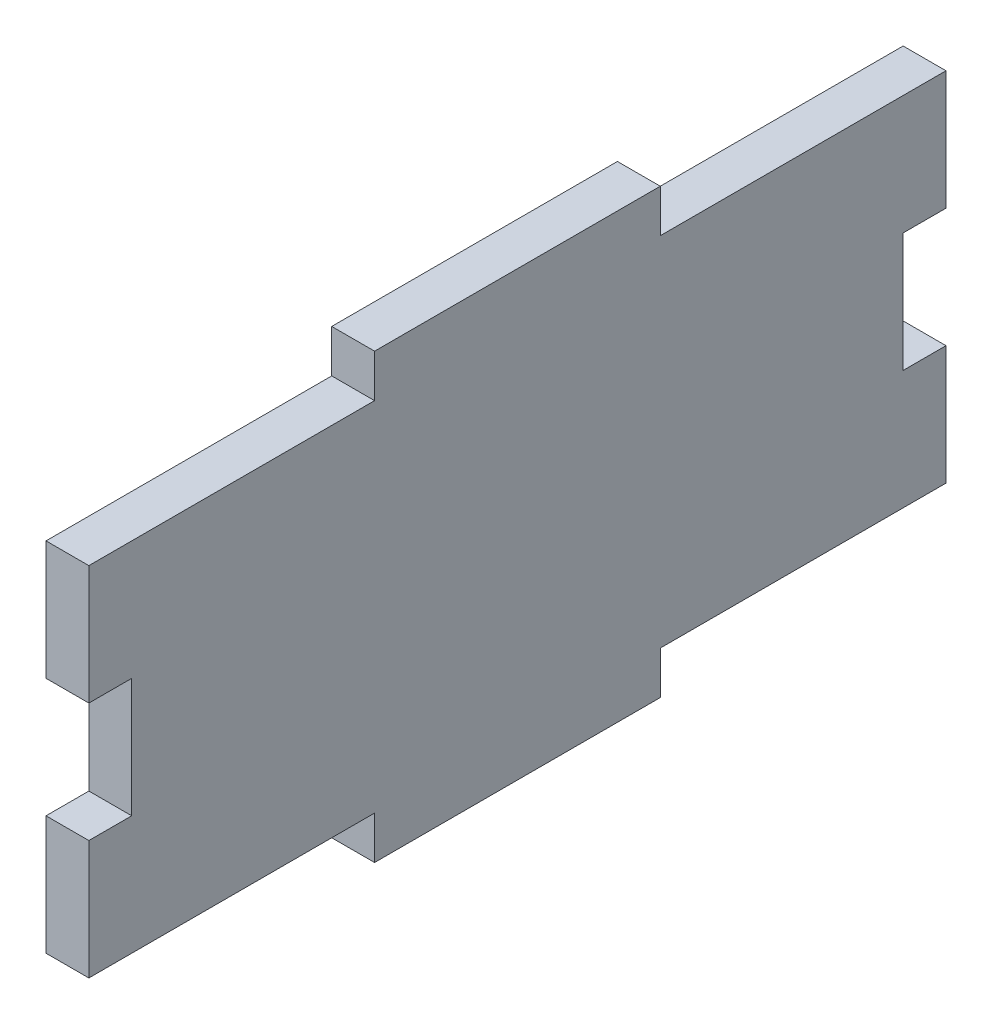
SolidWorks part; units mm, degrees
ref_plane "Front Plane" through (0, 0, 0) normal (0, 0, 1) x (1, 0, 0)
ref_plane "Top Plane" through (0, 0, 0) normal (0, 1, 0) x (1, 0, 0)
ref_plane "Right Plane" through (0, 0, 0) normal (1, 0, 0) x (0, 0, -1)
sketch "Sides" plane through (0, 0, 0) normal (1, 0, 0) x (0, 0, -1)
  line L0 (0, 16.6667) -> (0, 25)
  line L1 (0, 0) -> (20, 0)
  line L2 (0, 0) -> (0, 8.3333)
  line L3 (0, 25) -> (20, 25)
  line L4 (60, 0) -> (60, 8.3333)
  line L5 (0, 16.6667) -> (3, 16.6667)
  line L6 (40, 25) -> (60, 25)
  line L7 (0, 8.3333) -> (3, 8.3333)
  line L8 (3, 16.6667) -> (3, 8.3333)
  line L9 (40, 0) -> (60, 0)
  line L10 (20, 25) -> (20, 28)
  line L11 (20, 28) -> (40, 28)
  line L12 (40, 25) -> (40, 28)
  line L13 (60, 16.6667) -> (60, 25)
  line L14 (40, 0) -> (40, -3)
  line L15 (20, 0) -> (20, -3)
  line L16 (20, -3) -> (40, -3)
  line L17 (60, 16.6667) -> (57, 16.6667)
  line L18 (60, 8.3333) -> (57, 8.3333)
  line L19 (57, 16.6667) -> (57, 8.3333)
  spline B0 degree 3 poles (43.9007, 16.1432) (43.9696, 16.013) (44.0385, 15.9215) (44.0688, 15.8186) (44.1861, 15.4206) (44.4536, 15.3089) (44.8343, 15.3923) knots 92 92 92 92 93 93 93 94 94 94 94
  spline B1 degree 3 poles (43.6339, 15.6309) (43.6975, 15.7979) (43.7985, 15.9506) (43.9007, 16.1432) knots 91 91 91 91 92 92 92 92
  spline B2 degree 3 poles (43.0018, 15.3964) (43.0947, 15.3917) (43.1566, 15.3946) (43.2162, 15.3844) (43.4268, 15.3485) (43.5558, 15.4258) (43.6339, 15.6309) knots 89 89 89 89 90 90 90 91 91 91 91
  spline B3 degree 3 poles (43.5757, 16.3534) (43.383, 16.0453) (43.201, 15.7305) (43.0018, 15.3964) knots 88 88 88 88 89 89 89 89
  spline B4 degree 3 poles (43.0621, 17.5139) (43.249, 17.1881) (43.4076, 16.899) (43.58, 16.6183) (43.641, 16.5188) (43.6357, 16.4493) (43.5757, 16.3534) knots 86 86 86 86 87 87 87 88 88 88 88
  spline B5 degree 3 poles (43.9359, 16.8363) (43.8282, 17.0413) (43.7407, 17.2159) (43.6448, 17.3857) (43.6168, 17.4354) (43.5683, 17.5029) (43.5231, 17.508) (43.3821, 17.5239) (43.2381, 17.5139) (43.0621, 17.5139) knots 83 83 83 83 84 84 84 85 85 85 86 86 86 86
  spline B6 degree 3 poles (44.769, 17.5) (44.3221, 17.5403) (44.3228, 17.5399) (44.144, 17.2062) (44.0821, 17.0907) (44.0156, 16.9777) (43.9359, 16.8363) knots 81 81 81 81 82 82 82 83 83 83 83
  spline B7 degree 3 poles (44.2937, 16.7248) (44.4611, 16.9705) (44.6061, 17.2315) (44.769, 17.5) knots 80 80 80 80 81 81 81 81
  spline B8 degree 3 poles (44.8343, 15.4346) (44.6548, 15.727) (44.4833, 16.0248) (44.2925, 16.3097) (44.1922, 16.4593) (44.1918, 16.5754) (44.2937, 16.7248) knots 78 78 78 78 79 79 79 80 80 80 80
  spline B9 degree 3 poles (36.8757, 15.4021) (36.8757, 16.4401) (36.8757, 17.4613) (36.8757, 18.4826) knots 75 75 75 75 76 76 76 76
  spline B10 degree 3 poles (36.3889, 15.4021) (36.5643, 15.4021) (36.7145, 15.4021) (36.8757, 15.4021) knots 74 74 74 74 75 75 75 75
  spline B11 degree 3 poles (36.3677, 18.4826) (36.3747, 18.3992) (36.3878, 18.3157) (36.388, 18.2322) (36.3895, 17.3723) (36.3889, 16.5124) (36.3889, 15.6525) (36.3889, 15.5696) (36.3889, 15.4866) (36.3889, 15.4021) knots 71 71 71 71 72 72 72 73 73 73 74 74 74 74
  spline B12 degree 3 poles (34.096, 16.4603) (34.054, 15.8765) (34.3772, 15.4167) (34.8864, 15.3623) (35.1265, 15.3367) (35.3757, 15.3811) (35.6191, 15.408) (35.7791, 15.4258) (35.8461, 15.5147) (35.8435, 15.695) (35.8318, 16.4913) (35.8375, 17.2878) (35.8394, 18.0842) (35.8397, 18.2171) (35.8526, 18.3498) (35.8597, 18.4826) knots 65 65 65 65 66 66 66 67 67 67 68 68 68 69 69 69 70 70 70 70
  spline B13 degree 3 poles (35.3517, 17.5081) (35.257, 17.5202) (35.1877, 17.531) (35.1181, 17.5378) (34.7241, 17.5763) (34.3632, 17.3793) (34.2162, 17.0132) (34.1467, 16.8403) (34.1095, 16.6471) (34.096, 16.4603) knots 62 62 62 62 63 63 63 64 64 64 65 65 65 65
  spline B14 degree 3 poles (35.3517, 18.4826) (35.3517, 18.161) (35.3517, 17.8393) (35.3517, 17.5081) knots 61 61 61 61 62 62 62 62
  spline B15 degree 3 poles (31.9347, 16.5772) (31.8666, 15.9569) (32.1383, 15.4619) (32.6498, 15.3831) (32.9323, 15.3396) (33.2337, 15.4011) (33.5236, 15.4381) (33.5779, 15.4451) (33.6586, 15.5601) (33.659, 15.6256) (33.6656, 16.5779) (33.6606, 17.5303) (33.6583, 18.4826) knots 56 56 56 56 57 57 57 58 58 58 59 59 59 60 60 60 60
  spline B16 degree 3 poles (33.1927, 17.52) (32.3737, 17.5636) (32.0122, 17.2835) (31.9347, 16.5772) knots 55 55 55 55 56 56 56 56
  spline B17 degree 3 poles (33.1927, 18.4826) (33.1927, 18.1622) (33.1927, 17.8417) (33.1927, 17.52) knots 54 54 54 54 55 55 55 55
  spline B18 degree 3 poles (17.233, 15.096) (17.2467, 15.0359) (17.269, 14.9763) (17.2729, 14.9156) (17.3305, 14.0247) (17.4934, 13.1538) (17.7919, 12.3125) (18.513, 10.2803) (19.786, 8.7195) (21.7277, 7.7333) (21.8924, 7.6496) (22.0298, 7.6431) (22.2023, 7.7264) (23.0715, 8.1463) (23.8261, 8.7177) (24.4733, 9.4283) (25.9556, 11.0557) (26.6136, 13.013) (26.707, 15.1763) (26.7463, 16.0843) (26.7081, 16.9955) (26.7117, 17.9052) (26.7124, 18.0633) (26.6658, 18.1267) (26.4986, 18.1382) (25.3034, 18.2204) (24.1088, 18.3108) (22.9143, 18.4026) (22.6849, 18.4202) (22.4569, 18.4555) (22.2283, 18.4826) knots 43 43 43 43 44 44 44 45 45 45 46 46 46 47 47 47 48 48 48 49 49 49 50 50 50 51 51 51 52 52 52 53 53 53 53
  spline B19 degree 3 poles (27.9433, 10.336) (27.9433, 9.4175) (27.9433, 8.5102) (27.9433, 7.603) knots 40 40 40 40 41 41 41 41
  spline B20 degree 3 poles (28.2955, 10.336) (28.1664, 10.336) (28.0634, 10.336) (27.9433, 10.336) knots 39 39 39 39 40 40 40 40
  spline B21 degree 3 poles (28.2955, 7.8871) (28.2955, 8.7206) (28.2955, 9.5273) (28.2955, 10.336) knots 38 38 38 38 39 39 39 39
  spline B22 degree 3 poles (29.1295, 7.8871) (28.834, 7.8871) (28.5772, 7.8871) (28.2955, 7.8871) knots 37 37 37 37 38 38 38 38
  spline B23 degree 3 poles (29.0863, 7.603) (29.0991, 7.6872) (29.1119, 7.7714) (29.1295, 7.8871) knots 36 36 36 36 37 37 37 37
  spline B24 degree 3 poles (30.4833, 7.603) (30.7207, 7.7061) (30.8945, 7.8732) (30.9746, 8.1216) (31.0992, 8.5081) (31.1024, 8.898) (30.9668, 9.2823) (30.8503, 9.6123) (30.5913, 9.7938) (30.2469, 9.8032) (29.9056, 9.8126) (29.6328, 9.6421) (29.5054, 9.3162) (29.4498, 9.1739) (29.4151, 9.0194) (29.397, 8.8673) (29.3247, 8.259) (29.5198, 7.8422) (29.9753, 7.603) knots 29 29 29 29 30 30 30 31 31 31 32 32 32 33 33 33 34 34 34 35 35 35 35
  spline B25 degree 3 poles (33.0657, 7.603) (33.0685, 8.1439) (33.0827, 8.685) (33.0699, 9.2256) (33.0627, 9.5265) (32.8976, 9.7311) (32.5979, 9.7563) (32.2895, 9.7822) (31.9735, 9.7341) (31.6629, 9.699) (31.6143, 9.6935) (31.5412, 9.5853) (31.5405, 9.524) (31.5337, 8.8837) (31.5394, 8.2433) (31.5417, 7.603) knots 23 23 23 23 24 24 24 25 25 25 26 26 26 27 27 27 28 28 28 28
  spline B26 degree 3 poles (34.7964, 9.7546) (34.7149, 9.7608) (34.6589, 9.7641) (34.6031, 9.7694) (34.094, 9.8181) (33.7454, 9.5822) (33.6049, 9.0939) (33.4189, 8.4471) (33.6038, 7.9561) (34.1663, 7.603) knots 19 19 19 19 20 20 20 21 21 21 22 22 22 22
  spline B27 degree 3 poles (34.7964, 10.7255) (34.7964, 10.3977) (34.7964, 10.0791) (34.7964, 9.7546) knots 18 18 18 18 19 19 19 19
  spline B28 degree 3 poles (35.1611, 10.7255) (35.0272, 10.7255) (34.9243, 10.7255) (34.7964, 10.7255) knots 17 17 17 17 18 18 18 18
  spline B29 degree 3 poles (34.886, 7.603) (35.139, 7.6639) (35.1717, 7.8345) (35.1671, 8.0707) (35.1515, 8.8802) (35.1611, 9.6903) (35.1611, 10.5001) (35.1611, 10.5745) (35.1611, 10.6489) (35.1611, 10.7255) knots 14 14 14 14 15 15 15 16 16 16 17 17 17 17
  spline B30 degree 3 poles (36.7487, 7.603) (36.8756, 7.7184) (37.0467, 7.8108) (37.1215, 7.9536) (37.3785, 8.4443) (37.3837, 8.9613) (37.1172, 9.448) (36.8695, 9.9003) (36.1799, 9.9281) (35.8562, 9.5235) (35.4217, 8.9804) (35.605, 7.9513) (36.1983, 7.603) knots 9 9 9 9 10 10 10 11 11 11 12 12 12 13 13 13 13
  spline B31 degree 3 poles (39.3129, 9.2242) (39.301, 9.5315) (39.1224, 9.7344) (38.8143, 9.7619) (38.5257, 9.7877) (38.2298, 9.7413) (37.938, 9.7162) (37.8082, 9.705) (37.7593, 9.6258) (37.7612, 9.4851) (37.7695, 8.8578) (37.7647, 8.2304) (37.7647, 7.603) knots 4 4 4 4 5 5 5 6 6 6 7 7 7 8 8 8 8
  spline B32 degree 3 poles (39.2887, 7.603) (39.2994, 7.6288) (39.3194, 7.6546) (39.3194, 7.6805) (39.3204, 8.1951) (39.333, 8.7103) (39.3129, 9.2242) knots 2 2 2 2 3 3 3 4 4 4 4
  spline B33 degree 3 poles (28.2241, 15.3979) (28.2888, 16.0502) (28.3524, 16.6915) (28.4159, 17.3328) knots 15 15 15 15 16 16 16 16
  spline B34 degree 3 poles (27.7959, 15.3979) (27.9515, 15.3979) (28.0815, 15.3979) (28.2241, 15.3979) knots 14 14 14 14 15 15 15 15
  spline B35 degree 3 poles (28.0962, 18.093) (27.9961, 17.1939) (27.8966, 16.3011) (27.7959, 15.3979) knots 13 13 13 13 14 14 14 14
  spline B36 degree 3 poles (28.6144, 18.093) (28.4361, 18.093) (28.2756, 18.093) (28.0962, 18.093) knots 12 12 12 12 13 13 13 13
  spline B37 degree 3 poles (29.1658, 16.1257) (28.9701, 16.8241) (28.792, 17.4594) (28.6144, 18.093) knots 11 11 11 11 12 12 12 12
  spline B38 degree 3 poles (29.7366, 18.0939) (29.5509, 17.4535) (29.3663, 16.8172) (29.1658, 16.1257) knots 10 10 10 10 11 11 11 11
  spline B39 degree 3 poles (30.2541, 18.0939) (30.0681, 18.0939) (29.9072, 18.0939) (29.7366, 18.0939) knots 9 9 9 9 10 10 10 10
  spline B40 degree 3 poles (30.5558, 15.3989) (30.4542, 16.3064) (30.3543, 17.1992) (30.2541, 18.0939) knots 8 8 8 8 9 9 9 9
  spline B41 degree 3 poles (30.0748, 15.3989) (30.241, 15.3989) (30.392, 15.3989) (30.5558, 15.3989) knots 7 7 7 7 8 8 8 8
  spline B42 degree 3 poles (29.8838, 17.3298) (29.9472, 16.6888) (30.0106, 16.0478) (30.0748, 15.3989) knots 6 6 6 6 7 7 7 7
  spline B43 degree 3 poles (29.8593, 17.3332) (29.8675, 17.3321) (29.8756, 17.3309) (29.8838, 17.3298) knots 5 5 5 5 6 6 6 6
  spline B44 degree 3 poles (28.4414, 17.3366) (28.6091, 16.75) (28.7792, 16.1642) (28.9426, 15.5765) (28.9754, 15.4584) (29.002, 15.3768) (29.1581, 15.3793) (29.3096, 15.3817) (29.3227, 15.4711) (29.3523, 15.5748) (29.5197, 16.1614) (29.69, 16.7472) (29.8593, 17.3332) knots 1 1 1 1 2 2 2 3 3 3 4 4 4 5 5 5 5
  spline B45 degree 3 poles (28.4159, 17.3328) (28.4244, 17.334) (28.4329, 17.3353) (28.4414, 17.3366) knots 0 0 0 0 1 1 1 1
  spline B46 degree 3 poles (27.9024, 14.2791) (27.9024, 13.5852) (27.8849, 12.9029) (27.9092, 12.2221) (27.923, 11.8339) (28.2793, 11.5513) (28.692, 11.5336) (29.2176, 11.5111) (29.5793, 11.7377) (29.6706, 12.1478) (29.6782, 12.182) (29.6831, 12.2176) (29.6832, 12.2525) (29.6839, 12.9214) (29.6837, 13.5903) (29.6837, 14.279) knots 9 9 9 9 10 10 10 11 11 11 12 12 12 13 13 13 14 14 14 14
  spline B47 degree 3 poles (28.4018, 14.2791) (28.2163, 14.2791) (28.064, 14.2791) (27.9024, 14.2791) knots 8 8 8 8 9 9 9 9
  spline B48 degree 3 poles (29.2135, 14.279) (29.2135, 14.1906) (29.2135, 14.1145) (29.2135, 14.0384) (29.2135, 13.4749) (29.2165, 12.9113) (29.212, 12.3478) (29.21, 12.0973) (29.0566, 11.9332) (28.8335, 11.9222) (28.6031, 11.9109) (28.4314, 12.0726) (28.4088, 12.3259) (28.402, 12.4029) (28.4022, 12.4807) (28.4021, 12.5582) (28.4016, 13.0583) (28.4018, 13.5585) (28.4018, 14.0587) (28.4018, 14.1328) (28.4018, 14.207) (28.4018, 14.2791) knots 1 1 1 1 2 2 2 3 3 3 4 4 4 5 5 5 6 6 6 7 7 7 8 8 8 8
  spline B49 degree 3 poles (29.6837, 14.279) (29.5167, 14.279) (29.3731, 14.279) (29.2135, 14.279) knots 0 0 0 0 1 1 1 1
  spline B50 degree 3 poles (31.4148, 11.5831) (31.5892, 11.5831) (31.7291, 11.5831) (31.8952, 11.5831) knots 14 14 14 14 15 15 15 15
  spline B51 degree 3 poles (30.7161, 11.5845) (30.7161, 11.6689) (30.7161, 11.7448) (30.7161, 11.8206) (30.7161, 12.2784) (30.7141, 12.7363) (30.7185, 13.194) (30.7192, 13.2587) (30.7452, 13.3763) (30.7694, 13.379) (30.9258, 13.3961) (31.0982, 13.425) (31.2382, 13.3746) (31.3224, 13.3444) (31.4021, 13.1796) (31.4068, 13.0719) (31.4259, 12.6431) (31.4148, 12.213) (31.4148, 11.7834) (31.4148, 11.7169) (31.4148, 11.6504) (31.4148, 11.5831) knots 7 7 7 7 8 8 8 9 9 9 10 10 10 11 11 11 12 12 12 13 13 13 14 14 14 14
  spline B52 degree 3 poles (30.2225, 11.5845) (30.3987, 11.5845) (30.5446, 11.5845) (30.7161, 11.5845) knots 6 6 6 6 7 7 7 7
  spline B53 degree 3 poles (31.8952, 11.5831) (31.8952, 12.139) (31.9083, 12.6736) (31.8897, 13.2071) (31.8802, 13.4782) (31.6847, 13.6331) (31.4329, 13.6963) (31.0687, 13.7878) (30.7043, 13.7559) (30.352, 13.6371) (30.2934, 13.6173) (30.2299, 13.5089) (30.2282, 13.4399) (30.2171, 12.9965) (30.2225, 12.5526) (30.2225, 12.1089) (30.2225, 11.9357) (30.2225, 11.7625) (30.2225, 11.5845) knots 0 0 0 0 1 1 1 2 2 2 3 3 3 4 4 4 5 5 5 6 6 6 6
  spline B54 degree 3 poles (43.3169, 11.738) (43.3471, 11.6406) (43.3406, 11.5165) (43.3087, 11.4184) (43.2356, 11.1935) (43.1364, 10.9771) (43.0405, 10.7392) knots 10 10 10 10 11 11 11 12 12 12 12
  spline B55 degree 3 poles (42.7512, 13.4834) (42.9411, 12.902) (43.1361, 12.3222) (43.3169, 11.738) knots 9 9 9 9 10 10 10 10
  spline B56 degree 3 poles (42.6907, 13.6788) (42.7101, 13.6159) (42.7297, 13.5493) (42.7512, 13.4834) knots 8 8 8 8 9 9 9 9
  spline B57 degree 3 poles (43.6172, 12.1517) (43.5052, 12.5694) (43.4072, 12.9339) (43.3099, 13.2986) (43.1897, 13.749) (43.19, 13.7491) (42.7178, 13.6951) (42.7119, 13.6944) (42.7066, 13.6886) (42.6907, 13.6788) knots 5 5 5 5 6 6 6 7 7 7 8 8 8 8
  spline B58 degree 3 poles (43.979, 13.4368) (43.8859, 13.0221) (43.7508, 12.6168) (43.6172, 12.1517) knots 4 4 4 4 5 5 5 5
  spline B59 degree 3 poles (44.5225, 13.6954) (44.4473, 13.7) (44.3985, 13.6985) (44.3512, 13.7065) (44.1335, 13.7439) (44.0303, 13.6656) (43.979, 13.4368) knots 2 2 2 2 3 3 3 4 4 4 4
  spline B60 degree 3 poles (43.5584, 10.7392) (43.8783, 11.7202) (44.1978, 12.6999) (44.5225, 13.6954) knots 1 1 1 1 2 2 2 2
  spline B61 degree 3 poles (43.0405, 10.7392) (43.2271, 10.7392) (43.3865, 10.7392) (43.5584, 10.7392) knots 0 0 0 0 1 1 1 1
  spline B62 degree 3 poles (37.8282, 16.2724) (38.2356, 16.3332) (38.6454, 16.3943) (39.0542, 16.4553) knots 6 6 6 6 7 7 7 7
  spline B63 degree 3 poles (38.9017, 15.793) (38.1812, 15.574) (37.7603, 15.7636) (37.8282, 16.2724) knots 5 5 5 5 6 6 6 6
  spline B64 degree 3 poles (39.0092, 15.5097) (38.9739, 15.6027) (38.9376, 15.6984) (38.9017, 15.793) knots 4 4 4 4 5 5 5 5
  spline B65 degree 3 poles (39.0542, 16.4553) (39.1669, 16.946) (38.915, 17.4176) (38.483, 17.5281) (37.9716, 17.6589) (37.5208, 17.4127) (37.3836, 16.9077) (37.3364, 16.7343) (37.318, 16.5462) (37.3244, 16.3661) (37.3565, 15.4732) (38.2194, 15.03) (39.0092, 15.5097) knots 0 0 0 0 1 1 1 2 2 2 3 3 3 4 4 4 4
  spline B66 degree 3 poles (41.5556, 16.2705) (41.9713, 16.3323) (42.3887, 16.3944) (42.8673, 16.4655) knots 8 8 8 8 9 9 9 9
  spline B67 degree 3 poles (42.6521, 15.7797) (41.8376, 15.6235) (41.5473, 15.753) (41.5556, 16.2705) knots 7 7 7 7 8 8 8 8
  spline B68 degree 3 poles (42.7622, 15.492) (42.7204, 15.6012) (42.6858, 15.6916) (42.6521, 15.7797) knots 6 6 6 6 7 7 7 7
  spline B69 degree 3 poles (41.5566, 15.4573) (41.9546, 15.2601) (42.3579, 15.3185) (42.7622, 15.492) knots 5 5 5 5 6 6 6 6
  spline B70 degree 3 poles (41.1112, 16.8593) (41.0758, 16.7034) (41.0663, 16.5383) (41.0689, 16.3777) (41.0751, 15.9912) (41.1852, 15.6414) (41.5566, 15.4573) knots 3 3 3 3 4 4 4 5 5 5 5
  spline B71 degree 3 poles (42.8673, 16.4655) (42.8156, 16.6967) (42.7869, 16.9121) (42.7173, 17.1134) (42.6386, 17.341) (42.455, 17.4719) (42.2201, 17.5299) (41.6898, 17.6609) (41.2318, 17.3904) (41.1112, 16.8593) knots 0 0 0 0 1 1 1 2 2 2 3 3 3 3
  spline B72 degree 3 poles (35.8012, 12.4588) (36.2156, 12.5207) (36.6318, 12.5829) (37.0685, 12.6481) knots 7 7 7 7 8 8 8 8
  spline B73 degree 3 poles (36.8895, 11.9721) (36.1156, 11.7889) (35.7539, 11.9532) (35.8012, 12.4588) knots 6 6 6 6 7 7 7 7
  spline B74 degree 3 poles (36.9881, 11.7063) (36.9552, 11.795) (36.9218, 11.885) (36.8895, 11.9721) knots 5 5 5 5 6 6 6 6
  spline B75 degree 3 poles (35.3896, 13.1559) (35.3197, 12.8784) (35.2969, 12.565) (35.3488, 12.2854) (35.4807, 11.5741) (36.3929, 11.264) (36.9881, 11.7063) knots 3 3 3 3 4 4 4 5 5 5 5
  spline B76 degree 3 poles (37.0685, 12.6481) (37.0611, 12.7701) (37.0602, 12.8815) (37.0465, 12.9914) (36.9919, 13.427) (36.7329, 13.6996) (36.3422, 13.7387) (35.8722, 13.7857) (35.4979, 13.5855) (35.3896, 13.1559) knots 0 0 0 0 1 1 1 2 2 2 3 3 3 3
  spline B77 degree 3 poles (33.7844, 13.6967) (33.6138, 13.6967) (33.4537, 13.6967) (33.2614, 13.6967) knots 9 9 9 9 10 10 10 10
  spline B78 degree 3 poles (34.1875, 12.2323) (34.0537, 12.7185) (33.9198, 13.2047) (33.7844, 13.6967) knots 8 8 8 8 9 9 9 9
  spline B79 degree 3 poles (34.2301, 12.2267) (34.2159, 12.2286) (34.2017, 12.2304) (34.1875, 12.2323) knots 7 7 7 7 8 8 8 8
  spline B80 degree 3 poles (34.6441, 13.6943) (34.5043, 13.1987) (34.3672, 12.7127) (34.2301, 12.2267) knots 6 6 6 6 7 7 7 7
  spline B81 degree 3 poles (35.1036, 13.6943) (34.9376, 13.6943) (34.7926, 13.6943) (34.6441, 13.6943) knots 5 5 5 5 6 6 6 6
  spline B82 degree 3 poles (33.2614, 13.6967) (33.4876, 13.0001) (33.7035, 12.3318) (33.9244, 11.6652) (33.9365, 11.6287) (33.9861, 11.5887) (34.0251, 11.5797) (34.3186, 11.5115) (34.4232, 11.5737) (34.5125, 11.8573) (34.5294, 11.9109) (34.5492, 11.9636) (34.5664, 12.0172) (34.7442, 12.5719) (34.9218, 13.1266) (35.1036, 13.6943) knots 0 0 0 0 1 1 1 2 2 2 3 3 3 4 4 4 5 5 5 5
  spline B83 degree 3 poles (41.3954, 13.4015) (41.4715, 13.3874) (41.5382, 13.375) (41.6187, 13.3601) knots 13 13 13 13 14 14 14 14
  spline B84 degree 3 poles (41.3954, 13.6882) (41.3954, 13.5863) (41.3954, 13.4973) (41.3954, 13.4015) knots 12 12 12 12 13 13 13 13
  spline B85 degree 3 poles (41.5961, 13.7188) (41.5309, 13.7089) (41.4646, 13.6988) (41.3954, 13.6882) knots 11 11 11 11 12 12 12 12
  spline B86 degree 3 poles (42.1151, 14.3146) (41.9436, 14.2625) (41.7497, 14.2597) (41.6658, 14.1622) (41.5842, 14.0673) (41.6153, 13.8755) (41.5961, 13.7188) knots 9 9 9 9 10 10 10 11 11 11 11
  spline B87 degree 3 poles (42.1151, 13.7177) (42.1151, 13.9172) (42.1151, 14.0981) (42.1151, 14.3146) knots 8 8 8 8 9 9 9 9
  spline B88 degree 3 poles (42.4508, 13.6975) (42.3365, 13.7044) (42.2343, 13.7105) (42.1151, 13.7177) knots 7 7 7 7 8 8 8 8
  spline B89 degree 3 poles (42.4508, 13.3957) (42.4508, 13.5005) (42.4508, 13.5956) (42.4508, 13.6975) knots 6 6 6 6 7 7 7 7
  spline B90 degree 3 poles (42.1227, 13.3664) (42.2424, 13.3771) (42.3454, 13.3863) (42.4508, 13.3957) knots 5 5 5 5 6 6 6 6
  spline B91 degree 3 poles (42.1269, 12.0736) (42.1136, 12.5017) (42.1227, 12.9305) (42.1227, 13.3664) knots 4 4 4 4 5 5 5 5
  spline B92 degree 3 poles (42.4524, 11.8814) (42.2912, 11.8719) (42.1328, 11.8845) (42.1269, 12.0736) knots 3 3 3 3 4 4 4 4
  spline B93 degree 3 poles (42.4524, 11.6094) (42.4524, 11.6998) (42.4524, 11.7892) (42.4524, 11.8814) knots 2 2 2 2 3 3 3 3
  spline B94 degree 3 poles (41.6187, 13.3601) (41.6187, 12.939) (41.6079, 12.5233) (41.6216, 12.1084) (41.6367, 11.646) (42.0335, 11.4155) (42.4524, 11.6094) knots 0 0 0 0 1 1 1 2 2 2 2
  spline B95 degree 3 poles (39.4909, 15.7892) (39.4531, 15.6994) (39.4153, 15.6096) (39.3706, 15.5031) knots 15 15 15 15 16 16 16 16
  spline B96 degree 3 poles (40.2083, 15.9048) (40.1601, 15.7383) (40.0184, 15.6804) (39.8579, 15.6991) (39.7367, 15.7132) (39.6188, 15.7567) (39.4909, 15.7892) knots 13 13 13 13 14 14 14 15 15 15 15
  spline B97 degree 3 poles (40.6622, 17.4042) (40.4059, 17.5624) (40.1466, 17.5947) (39.8786, 17.5224) (39.6142, 17.4511) (39.4654, 17.2654) (39.428, 16.9949) (39.3947, 16.7532) (39.5154, 16.5386) (39.7569, 16.4089) (39.8434, 16.3624) (39.9356, 16.3267) (40.0248, 16.2851) (40.1893, 16.2084) (40.2575, 16.0748) (40.2083, 15.9048) knots 8 8 8 8 9 9 9 10 10 10 11 11 11 12 12 12 13 13 13 13
  spline B98 degree 3 poles (40.5572, 17.1398) (40.5934, 17.231) (40.6262, 17.3137) (40.6622, 17.4042) knots 7 7 7 7 8 8 8 8
  spline B99 degree 3 poles (40.0705, 16.7053) (39.9316, 16.7848) (39.8689, 16.9045) (39.9285, 17.0605) (39.9853, 17.2092) (40.1134, 17.2484) (40.2569, 17.2252) (40.3566, 17.2091) (40.4527, 17.1704) (40.5572, 17.1398) knots 4 4 4 4 5 5 5 6 6 6 7 7 7 7
  spline B100 degree 3 poles (40.7265, 15.9403) (40.7538, 16.2324) (40.6249, 16.4357) (40.317, 16.5857) (40.2349, 16.6257) (40.1496, 16.6601) (40.0705, 16.7053) knots 2 2 2 2 3 3 3 4 4 4 4
  spline B101 degree 3 poles (39.3706, 15.5031) (39.6369, 15.3408) (39.9074, 15.3159) (40.1825, 15.3708) (40.4927, 15.4327) (40.7006, 15.6625) (40.7265, 15.9403) knots 0 0 0 0 1 1 1 2 2 2 2
  spline B102 degree 3 poles (38.7717, 13.21) (38.7313, 12.9322) (38.8372, 12.7299) (39.1027, 12.5887) (39.1893, 12.5426) (39.2817, 12.5078) (39.3706, 12.4659) (39.5289, 12.3913) (39.5815, 12.2591) (39.5408, 12.099) (39.4974, 11.9278) (39.3582, 11.8689) (39.1987, 11.8855) (39.0768, 11.8982) (38.9585, 11.9452) (38.8249, 11.9805) knots 11 11 11 11 12 12 12 13 13 13 14 14 14 15 15 15 16 16 16 16
  spline B103 degree 3 poles (39.9934, 13.5869) (39.7626, 13.7481) (39.5135, 13.7712) (39.2599, 13.7244) (38.9885, 13.6744) (38.81, 13.4733) (38.7717, 13.21) knots 9 9 9 9 10 10 10 11 11 11 11
  spline B104 degree 3 poles (39.892, 13.328) (39.9255, 13.4137) (39.9583, 13.4975) (39.9934, 13.5869) knots 8 8 8 8 9 9 9 9
  spline B105 degree 3 poles (39.2649, 13.2372) (39.3204, 13.3258) (39.4556, 13.3936) (39.5646, 13.4108) (39.6633, 13.4264) (39.7748, 13.3609) (39.892, 13.328) knots 6 6 6 6 7 7 7 8 8 8 8
  spline B106 degree 3 poles (40.0542, 12.1007) (40.0885, 12.4078) (39.9731, 12.6114) (39.676, 12.7629) (39.5822, 12.8107) (39.4818, 12.8469) (39.3918, 12.9007) (39.2634, 12.9775) (39.1847, 13.1094) (39.2649, 13.2372) knots 3 3 3 3 4 4 4 5 5 5 6 6 6 6
  spline B107 degree 3 poles (38.7138, 11.7008) (38.9565, 11.5384) (39.2834, 11.4882) (39.5528, 11.5653) (39.8392, 11.6473) (40.0258, 11.8466) (40.0542, 12.1007) knots 1 1 1 1 2 2 2 3 3 3 3
  spline B108 degree 3 poles (38.8249, 11.9805) (38.7886, 11.8893) (38.7506, 11.7935) (38.7138, 11.7008) knots 0 0 0 0 1 1 1 1
  spline B109 degree 3 poles (38.4417, 13.411) (38.4685, 13.5067) (38.4965, 13.6072) (38.5397, 13.7618) knots 8 8 8 8 9 9 9 9
  spline B110 degree 3 poles (37.9832, 11.5938) (37.9832, 12.0832) (37.9832, 12.5543) (37.9832, 13.0254) (37.9831, 13.4288) (37.9831, 13.4287) (38.3934, 13.3967) (38.4061, 13.3957) (38.4195, 13.4041) (38.4417, 13.411) knots 5 5 5 5 6 6 6 7 7 7 8 8 8 8
  spline B111 degree 3 poles (37.5038, 11.5938) (37.6771, 11.5938) (37.8257, 11.5938) (37.9832, 11.5938) knots 4 4 4 4 5 5 5 5
  spline B112 degree 3 poles (38.5397, 13.7618) (38.262, 13.7357) (38.0181, 13.7163) (37.7751, 13.6888) (37.5714, 13.6658) (37.4733, 13.5664) (37.499, 13.3411) (37.5219, 13.1397) (37.5038, 12.9336) (37.5038, 12.7295) (37.5038, 12.3518) (37.5038, 11.974) (37.5038, 11.5938) knots 0 0 0 0 1 1 1 2 2 2 3 3 3 4 4 4 4
  spline B113 degree 3 poles (31.0126, 15.3942) (31.1724, 15.3942) (31.318, 15.3942) (31.478, 15.3942) knots 3 3 3 3 4 4 4 4
  spline B114 degree 3 poles (31.0126, 17.4988) (31.0126, 16.7887) (31.0126, 16.0958) (31.0126, 15.3942) knots 2 2 2 2 3 3 3 3
  spline B115 degree 3 poles (31.478, 17.4988) (31.3135, 17.4988) (31.1635, 17.4988) (31.0126, 17.4988) knots 1 1 1 1 2 2 2 2
  spline B116 degree 3 poles (31.478, 15.3942) (31.478, 16.1125) (31.478, 16.8054) (31.478, 17.4988) knots 0 0 0 0 1 1 1 1
  spline B117 degree 3 poles (32.9063, 11.5872) (32.9063, 12.2932) (32.9063, 12.9876) (32.9063, 13.6934) knots 3 3 3 3 4 4 4 4
  spline B118 degree 3 poles (32.4413, 11.5872) (32.6046, 11.5872) (32.7501, 11.5872) (32.9063, 11.5872) knots 2 2 2 2 3 3 3 3
  spline B119 degree 3 poles (32.4413, 13.6934) (32.4413, 12.9822) (32.4413, 12.2835) (32.4413, 11.5872) knots 1 1 1 1 2 2 2 2
  spline B120 degree 3 poles (32.9063, 13.6934) (32.7449, 13.6934) (32.5946, 13.6934) (32.4413, 13.6934) knots 0 0 0 0 1 1 1 1
  spline B121 degree 3 poles (40.4924, 11.5881) (40.6545, 11.5881) (40.8056, 11.5881) (40.9691, 11.5881) knots 3 3 3 3 4 4 4 4
  spline B122 degree 3 poles (40.4924, 13.6928) (40.4924, 12.9868) (40.4924, 12.2938) (40.4924, 11.5881) knots 2 2 2 2 3 3 3 3
  spline B123 degree 3 poles (40.9691, 13.6928) (40.805, 13.6928) (40.6539, 13.6928) (40.4924, 13.6928) knots 1 1 1 1 2 2 2 2
  spline B124 degree 3 poles (40.9691, 11.5881) (40.9691, 12.3024) (40.9691, 12.996) (40.9691, 13.6928) knots 0 0 0 0 1 1 1 1
  spline B125 degree 3 poles (41.0002, 14.3103) (40.9898, 14.4732) (40.8846, 14.5365) (40.7369, 14.5474) knots 3 3 3 3 4 4 4 4
  spline B126 degree 3 poles (40.7369, 14.5474) (40.5825, 14.5376) (40.4761, 14.4703) (40.4712, 14.3088) (40.4661, 14.1431) (40.5777, 14.0743) (40.7255, 14.0636) (40.8843, 14.0521) (41.0094, 14.1666) (41.0002, 14.3103) knots 0 0 0 0 1 1 1 2 2 2 3 3 3 3
  spline B127 degree 3 poles (32.4005, 14.3031) (32.411, 14.1444) (32.516, 14.0743) (32.6667, 14.0623) knots 3 3 3 3 4 4 4 4
  spline B128 degree 3 poles (32.9362, 14.2971) (32.9346, 14.4589) (32.8364, 14.5348) (32.6833, 14.5444) (32.5254, 14.5543) (32.3912, 14.4441) (32.4005, 14.3031) knots 1 1 1 1 2 2 2 3 3 3 3
  spline B129 degree 3 poles (32.6667, 14.0623) (32.814, 14.0604) (32.9374, 14.1626) (32.9362, 14.2971) knots 0 0 0 0 1 1 1 1
  spline B130 degree 3 poles (30.9864, 18.113) (30.9873, 17.9411) (31.1017, 17.8871) (31.2384, 17.878) knots 3 3 3 3 4 4 4 4
  spline B131 degree 3 poles (31.2384, 17.878) (31.4085, 17.8857) (31.5144, 17.9605) (31.5112, 18.1224) (31.508, 18.2839) (31.3971, 18.3602) (31.2429, 18.3574) (31.0893, 18.3546) (30.9856, 18.2798) (30.9864, 18.113) knots 0 0 0 0 1 1 1 2 2 2 3 3 3 3
  spline B132 degree 3 poles (21.6357, 18.4826) (21.8332, 18.4826) (22.0308, 18.4826) (22.2283, 18.4826) knots 14 14 14 14 15 15 15 15
  spline B133 degree 3 poles (17.2919, 18.1328) (18.47, 18.2206) (19.6361, 18.3057) (20.8018, 18.3954) (21.0803, 18.4168) (21.3577, 18.4531) (21.6357, 18.4826) knots 12 12 12 12 13 13 13 14 14 14 14
  spline B134 degree 3 poles (17.233, 17.6783) (17.2523, 17.8275) (17.2717, 17.9767) (17.2919, 18.1328) knots 11 11 11 11 12 12 12 12
  spline B135 degree 3 poles (17.233, 15.096) (17.233, 15.9567) (17.233, 16.8175) (17.233, 17.6783) knots 10 10 10 10 11 11 11 11
  spline B136 degree 3 poles (22.2283, 18.4826) (22.4569, 18.4555) (22.6849, 18.4202) (22.9143, 18.4026) (24.1088, 18.3108) (25.3034, 18.2204) (26.4986, 18.1382) (26.6658, 18.1267) (26.7124, 18.0633) (26.7117, 17.9052) (26.7081, 16.9955) (26.7463, 16.0843) (26.707, 15.1763) (26.6136, 13.013) (25.9556, 11.0557) (24.4733, 9.4283) (23.8261, 8.7177) (23.0715, 8.1463) (22.2023, 7.7264) (22.0298, 7.6431) (21.8924, 7.6496) (21.7277, 7.7333) (19.786, 8.7195) (18.513, 10.2803) (17.7919, 12.3125) (17.4934, 13.1538) (17.3305, 14.0247) (17.2729, 14.9156) (17.269, 14.9763) (17.2467, 15.0359) (17.233, 15.096) knots 0 0 0 0 1 1 1 2 2 2 3 3 3 4 4 4 5 5 5 6 6 6 7 7 7 8 8 8 9 9 9 10 10 10 10
  spline B137 degree 3 poles (25.3619, 12.7625) (25.2958, 12.9159) (25.2736, 13.0544) (25.1936, 13.1368) (24.9656, 13.3715) (24.7422, 13.6306) (24.4663, 13.7954) (23.699, 14.2539) (22.8372, 14.3576) (21.9602, 14.3443) (21.2977, 14.3343) (20.667, 14.1588) (19.9907, 13.9032) knots 24 24 24 24 25 25 25 26 26 26 27 27 27 28 28 28 28
  spline B138 degree 3 poles (20.3345, 13.4321) (21.085, 13.6323) (21.876, 13.6643) (22.6666, 13.4317) (22.8074, 13.3903) (22.9052, 13.3768) (23.0118, 13.505) (23.1096, 13.6225) (23.2562, 13.6862) (23.4106, 13.6049) (23.5718, 13.52) (23.619, 13.353) (23.5615, 13.2043) (23.4809, 12.9962) (23.6014, 12.9058) (23.7268, 12.803) (23.7521, 12.7822) (23.7889, 12.7644) (23.8204, 12.7642) (24.3181, 12.7618) (24.8158, 12.7625) (25.3619, 12.7625) knots 17 17 17 17 18 18 18 19 19 19 20 20 20 21 21 21 22 22 22 23 23 23 24 24 24 24
  spline B139 degree 3 poles (20.0473, 13.2182) (20.004, 13.163) (19.9532, 13.1121) (19.9195, 13.0516) (19.8883, 12.9954) (19.8461, 12.919) (19.8629, 12.8702) (19.8794, 12.8222) (19.9752, 12.7593) (20.0165, 12.7712) (20.0965, 12.7943) (20.2011, 12.851) (20.2265, 12.9194) (20.2831, 13.0713) (20.297, 13.2391) (20.3345, 13.4321) knots 12 12 12 12 13 13 13 14 14 14 15 15 15 16 16 16 17 17 17 17
  spline B140 degree 3 poles (20.0025, 13.2749) (20.0175, 13.256) (20.0324, 13.2371) (20.0473, 13.2182) knots 11 11 11 11 12 12 12 12
  spline B141 degree 3 poles (19.9907, 13.9032) (20.0379, 14.0165) (20.0757, 14.082) (20.0919, 14.1526) (20.1109, 14.2353) (20.1499, 14.3553) (20.1114, 14.4009) (20.0259, 14.5021) (19.9009, 14.4531) (19.849, 14.3511) (19.791, 14.2371) (19.7548, 14.1025) (19.7477, 13.9748) (19.7405, 13.8441) (19.7184, 13.7591) (19.5727, 13.7456) (19.5332, 13.7419) (19.4948, 13.7197) (19.4574, 13.7028) (19.2237, 13.5967) (18.9934, 13.4823) (18.756, 13.3855) (18.5821, 13.3145) (18.5959, 13.1813) (18.6348, 13.0526) (18.6743, 12.9216) (18.7733, 12.8234) (18.9231, 12.88) (19.1424, 12.9628) (19.3503, 13.0755) (19.5692, 13.1596) (19.7079, 13.2129) (19.8577, 13.2374) (20.0025, 13.2749) knots 0 0 0 0 1 1 1 2 2 2 3 3 3 4 4 4 5 5 5 6 6 6 7 7 7 8 8 8 9 9 9 10 10 10 11 11 11 11
  spline B142 degree 3 poles (20.3874, 11.2955) (20.3729, 11.2619) (20.3689, 11.2483) (20.3617, 11.2367) (20.322, 11.1714) (20.2721, 11.1097) (20.2483, 11.0392) (20.2427, 11.0226) (20.3394, 10.9408) (20.3633, 10.9507) (20.4416, 10.9833) (20.5384, 11.0295) (20.572, 11.098) (20.6222, 11.2002) (20.6247, 11.3258) (20.6513, 11.4607) knots 20 20 20 20 21 21 21 22 22 22 23 23 23 24 24 24 25 25 25 25
  spline B143 degree 3 poles (20.4609, 12.3106) (20.3873, 12.294) (20.2803, 12.3013) (20.2475, 12.2555) (20.1906, 12.1762) (20.1591, 12.0648) (20.1546, 11.9652) (20.1493, 11.8454) (20.1268, 11.7799) (20, 11.7322) (19.7545, 11.64) (19.5169, 11.5242) (19.2831, 11.4043) (19.1589, 11.3406) (19.1478, 11.2089) (19.2279, 11.1154) (19.2824, 11.0518) (19.4116, 10.9904) (19.4807, 11.0123) (19.7456, 11.0961) (19.9988, 11.2163) (20.259, 11.3164) (20.2926, 11.3293) (20.341, 11.304) (20.3874, 11.2955) knots 12 12 12 12 13 13 13 14 14 14 15 15 15 16 16 16 17 17 17 18 18 18 19 19 19 20 20 20 20
  spline B144 degree 3 poles (20.3692, 11.9007) (20.4164, 11.9934) (20.4555, 12.0413) (20.4641, 12.0941) (20.4754, 12.1643) (20.4631, 12.2383) (20.4609, 12.3106) knots 10 10 10 10 11 11 11 12 12 12 12
  spline B145 degree 3 poles (24.7415, 10.9495) (24.6232, 11.1449) (24.5633, 11.3116) (24.448, 11.419) (24.26, 11.5943) (24.0539, 11.7698) (23.8237, 11.8768) (23.0479, 12.2376) (22.2279, 12.3197) (21.389, 12.1582) (21.0626, 12.0954) (20.7431, 11.9964) (20.3692, 11.9007) knots 6 6 6 6 7 7 7 8 8 8 9 9 9 10 10 10 10
  spline B146 degree 3 poles (20.6513, 11.4607) (21.2238, 11.613) (21.8121, 11.6777) (22.407, 11.5133) (22.5224, 11.4813) (22.5984, 11.4871) (22.6826, 11.5835) (22.786, 11.702) (22.9485, 11.7771) (23.0744, 11.6681) (23.1616, 11.5926) (23.2023, 11.4309) (23.2101, 11.3044) (23.2196, 11.1491) (23.3022, 10.9605) (23.4564, 10.9547) (23.8604, 10.9393) (24.2655, 10.9495) (24.7415, 10.9495) knots 0 0 0 0 1 1 1 2 2 2 3 3 3 4 4 4 5 5 5 6 6 6 6
  spline B147 degree 3 poles (20.4719, 16.7815) (20.6537, 16.7581) (20.699, 16.6132) (20.7271, 16.4535) (20.76, 16.2663) (20.8032, 16.0805) (20.8276, 15.8923) (20.852, 15.7043) (20.9443, 15.5771) (21.1205, 15.5152) (21.6856, 15.3168) (22.2527, 15.3173) (22.8177, 15.514) (22.9829, 15.5716) (23.0804, 15.6877) (23.1031, 15.8713) (23.1273, 16.0666) (23.1727, 16.2592) (23.2059, 16.4535) (23.2334, 16.6147) (23.2819, 16.7568) (23.472, 16.7809) knots 20 20 20 20 21 21 21 22 22 22 23 23 23 24 24 24 25 25 25 26 26 26 27 27 27 27
  spline B148 degree 3 poles (21.1104, 16.4729) (21.0469, 16.6023) (20.9066, 16.7538) (20.9358, 16.858) (20.9877, 17.0437) (20.866, 17.1182) (20.7912, 17.21) (20.7482, 17.2627) (20.6002, 17.2844) (20.537, 17.2504) (20.4738, 17.2164) (20.4399, 17.0984) (20.4257, 17.0118) (20.4145, 16.9435) (20.4527, 16.8671) (20.4719, 16.7815) knots 15 15 15 15 16 16 16 17 17 17 18 18 18 19 19 19 20 20 20 20
  spline B149 degree 3 poles (21.6926, 17.2446) (21.8074, 17.1082) (21.8381, 16.7202) (21.7393, 16.5942) (21.7207, 16.5706) (21.6813, 16.5564) (21.6493, 16.5513) (21.4777, 16.5239) (21.3054, 16.5008) (21.1104, 16.4729) knots 12 12 12 12 13 13 13 14 14 14 15 15 15 15
  spline B150 degree 3 poles (22.8015, 16.4662) (22.6693, 16.4911) (22.5467, 16.5209) (22.4223, 16.5359) (22.2897, 16.5519) (22.1438, 16.5318) (22.1464, 16.7365) (22.1481, 16.8675) (22.0771, 17.0522) (22.1393, 17.1188) (22.2716, 17.2605) (22.1977, 17.3853) (22.163, 17.5004) (22.1423, 17.5691) (22.0199, 17.6521) (21.9478, 17.6479) (21.8763, 17.6438) (21.7946, 17.5488) (21.747, 17.4747) (21.7068, 17.4121) (21.7091, 17.3223) (21.6926, 17.2446) knots 5 5 5 5 6 6 6 7 7 7 8 8 8 9 9 9 10 10 10 11 11 11 12 12 12 12
  spline B151 degree 3 poles (23.472, 16.7809) (23.478, 16.8431) (23.4906, 16.8964) (23.4864, 16.9482) (23.4786, 17.0448) (23.4856, 17.1564) (23.438, 17.2308) (23.41, 17.2745) (23.2622, 17.2955) (23.215, 17.2616) (23.1207, 17.1939) (22.9773, 17.0556) (22.9976, 16.9919) (23.0761, 16.7445) (22.8831, 16.6361) (22.8015, 16.4662) knots 0 0 0 0 1 1 1 2 2 2 3 3 3 4 4 4 5 5 5 5
  spline B152 degree 3 poles (20.9968, 9.7947) (21.3908, 9.8996) (21.7914, 9.9314) (22.2018, 9.862) (22.2776, 9.8492) (22.3632, 9.8938) (22.4441, 9.9123) (22.5471, 9.9359) (22.6817, 10.0106) (22.7449, 9.9711) (22.8236, 9.9218) (22.8883, 9.774) (22.8788, 9.6766) (22.8614, 9.4993) (22.9641, 9.426) (23.0835, 9.4177) (23.3834, 9.3967) (23.6857, 9.4107) (24.0024, 9.4107) knots 17 17 17 17 18 18 18 19 19 19 20 20 20 21 21 21 22 22 22 23 23 23 23
  spline B153 degree 3 poles (20.7377, 9.6664) (20.7089, 9.5687) (20.6782, 9.4899) (20.668, 9.4084) (20.666, 9.3926) (20.7669, 9.3388) (20.7805, 9.3502) (20.8516, 9.4096) (20.9254, 9.4761) (20.9674, 9.5564) (21.0001, 9.6189) (20.9877, 9.705) (20.9968, 9.7947) knots 13 13 13 13 14 14 14 15 15 15 16 16 16 17 17 17 17
  spline B154 degree 3 poles (20.8423, 10.5084) (20.7796, 10.4961) (20.6879, 10.5048) (20.6604, 10.4669) (20.6106, 10.3982) (20.5789, 10.3023) (20.5766, 10.2168) (20.5735, 10.1033) (20.5547, 10.0486) (20.4288, 10.0104) (20.2476, 9.9555) (20.0731, 9.8654) (19.9119, 9.7645) (19.8602, 9.7321) (19.8224, 9.602) (19.8465, 9.5458) (19.8697, 9.4913) (19.9935, 9.4314) (20.0508, 9.4485) (20.2596, 9.5109) (20.4581, 9.6067) (20.6628, 9.6837) (20.6898, 9.6939) (20.7301, 9.6684) (20.7377, 9.6664) knots 5 5 5 5 6 6 6 7 7 7 8 8 8 9 9 9 10 10 10 11 11 11 12 12 12 13 13 13 13
  spline B155 degree 3 poles (20.764, 10.1709) (20.8041, 10.2383) (20.8433, 10.2782) (20.851, 10.3235) (20.8611, 10.3829) (20.8464, 10.4466) (20.8423, 10.5084) knots 3 3 3 3 4 4 4 5 5 5 5
  spline B156 degree 3 poles (24.0024, 9.4107) (23.9407, 9.7164) (23.8028, 9.9007) (23.4991, 10.0663) (22.9421, 10.37) (22.3374, 10.4434) (21.7184, 10.3745) (21.4103, 10.3403) (21.1088, 10.2466) (20.764, 10.1709) knots 0 0 0 0 1 1 1 2 2 2 3 3 3 3
  spline B157 degree 3 poles (35.3517, 18.4826) (35.521, 18.4826) (35.6903, 18.4826) (35.8597, 18.4826) knots 9 9 9 9 10 10 10 10
  spline B158 degree 3 poles (35.3517, 17.5081) (35.3517, 17.8393) (35.3517, 18.161) (35.3517, 18.4826) knots 8 8 8 8 9 9 9 9
  spline B159 degree 3 poles (34.096, 16.4603) (34.1095, 16.6471) (34.1467, 16.8403) (34.2162, 17.0132) (34.3632, 17.3793) (34.7241, 17.5763) (35.1181, 17.5378) (35.1877, 17.531) (35.257, 17.5202) (35.3517, 17.5081) knots 5 5 5 5 6 6 6 7 7 7 8 8 8 8
  spline B160 degree 3 poles (35.8597, 18.4826) (35.8526, 18.3498) (35.8397, 18.2171) (35.8394, 18.0842) (35.8375, 17.2878) (35.8318, 16.4913) (35.8435, 15.695) (35.8461, 15.5147) (35.7791, 15.4258) (35.6191, 15.408) (35.3757, 15.3811) (35.1265, 15.3367) (34.8864, 15.3623) (34.3772, 15.4167) (34.054, 15.8765) (34.096, 16.4603) knots 0 0 0 0 1 1 1 2 2 2 3 3 3 4 4 4 5 5 5 5
  spline B161 degree 3 poles (34.6294, 16.1135) (34.6912, 15.7231) (34.9439, 15.5923) (35.3518, 15.7092) knots 4 4 4 4 5 5 5 5
  spline B162 degree 3 poles (35.3518, 15.7092) (35.3518, 16.1252) (35.3518, 16.5334) (35.3518, 16.9417) (35.3518, 17.2565) (35.1893, 17.3624) (34.9109, 17.1972) (34.7954, 17.1287) (34.6744, 16.9885) (34.651, 16.8632) (34.6055, 16.6195) (34.5907, 16.3575) (34.6294, 16.1135) knots 0 0 0 0 1 1 1 2 2 2 3 3 3 4 4 4 4
  spline B163 degree 3 poles (33.1927, 18.4826) (33.3479, 18.4826) (33.5031, 18.4826) (33.6583, 18.4826) knots 6 6 6 6 7 7 7 7
  spline B164 degree 3 poles (33.1927, 17.52) (33.1927, 17.8417) (33.1927, 18.1622) (33.1927, 18.4826) knots 5 5 5 5 6 6 6 6
  spline B165 degree 3 poles (31.9347, 16.5772) (32.0122, 17.2835) (32.3737, 17.5636) (33.1927, 17.52) knots 4 4 4 4 5 5 5 5
  spline B166 degree 3 poles (33.6583, 18.4826) (33.6606, 17.5303) (33.6656, 16.5779) (33.659, 15.6256) (33.6586, 15.5601) (33.5779, 15.4451) (33.5236, 15.4381) (33.2337, 15.4011) (32.9323, 15.3396) (32.6498, 15.3831) (32.1383, 15.4619) (31.8666, 15.9569) (31.9347, 16.5772) knots 0 0 0 0 1 1 1 2 2 2 3 3 3 4 4 4 4
  spline B167 degree 3 poles (32.4937, 16.8938) (32.4436, 16.6307) (32.4296, 16.3468) (32.4714, 16.0835) (32.5306, 15.7114) (32.8017, 15.586) (33.1846, 15.7135) knots 3 3 3 3 4 4 4 5 5 5 5
  spline B168 degree 3 poles (33.1846, 15.7135) (33.1846, 16.1842) (33.1874, 16.6619) (33.1792, 17.1395) (33.1785, 17.1775) (33.1068, 17.2375) (33.0596, 17.2476) (32.8082, 17.3013) (32.5448, 17.1612) (32.4937, 16.8938) knots 0 0 0 0 1 1 1 2 2 2 3 3 3 3
  spline B169 degree 3 poles (34.886, 7.603) (34.6461, 7.603) (34.4062, 7.603) (34.1663, 7.603) knots 8 8 8 8 9 9 9 9
  spline B170 degree 3 poles (35.1611, 10.7255) (35.1611, 10.6489) (35.1611, 10.5745) (35.1611, 10.5001) (35.1611, 9.6903) (35.1515, 8.8802) (35.1671, 8.0707) (35.1717, 7.8345) (35.139, 7.6639) (34.886, 7.603) knots 5 5 5 5 6 6 6 7 7 7 8 8 8 8
  spline B171 degree 3 poles (34.7964, 10.7255) (34.9243, 10.7255) (35.0272, 10.7255) (35.1611, 10.7255) knots 4 4 4 4 5 5 5 5
  spline B172 degree 3 poles (34.7964, 9.7546) (34.7964, 10.0791) (34.7964, 10.3977) (34.7964, 10.7255) knots 3 3 3 3 4 4 4 4
  spline B173 degree 3 poles (34.1663, 7.603) (33.6038, 7.9561) (33.4189, 8.4471) (33.6049, 9.0939) (33.7454, 9.5822) (34.094, 9.8181) (34.6031, 9.7694) (34.6589, 9.7641) (34.7149, 9.7608) (34.7964, 9.7546) knots 0 0 0 0 1 1 1 2 2 2 3 3 3 3
  spline B174 degree 3 poles (34.8013, 7.9003) (34.8013, 8.4016) (34.8015, 8.9081) (34.8009, 9.4146) (34.8008, 9.4488) (34.7947, 9.4829) (34.7905, 9.5269) knots 3 3 3 3 4 4 4 5 5 5 5
  spline B175 degree 3 poles (34.7905, 9.5269) (34.3451, 9.6179) (34.0461, 9.4934) (33.9746, 9.1265) (33.9186, 8.839) (33.9185, 8.5216) (33.9784, 8.2352) (34.0583, 7.8538) (34.4279, 7.7242) (34.8013, 7.9003) knots 0 0 0 0 1 1 1 2 2 2 3 3 3 3
  spline B176 degree 3 poles (44.8343, 15.4346) (44.8343, 15.4205) (44.8343, 15.4064) (44.8343, 15.3923) knots 16 16 16 16 17 17 17 17
  spline B177 degree 3 poles (44.2937, 16.7248) (44.1918, 16.5754) (44.1922, 16.4593) (44.2925, 16.3097) (44.4833, 16.0248) (44.6548, 15.727) (44.8343, 15.4346) knots 14 14 14 14 15 15 15 16 16 16 16
  spline B178 degree 3 poles (44.769, 17.5) (44.6061, 17.2315) (44.4611, 16.9705) (44.2937, 16.7248) knots 13 13 13 13 14 14 14 14
  spline B179 degree 3 poles (43.9359, 16.8363) (44.0156, 16.9777) (44.0821, 17.0907) (44.144, 17.2062) (44.3228, 17.5399) (44.3221, 17.5403) (44.769, 17.5) knots 11 11 11 11 12 12 12 13 13 13 13
  spline B180 degree 3 poles (43.0621, 17.5139) (43.2381, 17.5139) (43.3821, 17.5239) (43.5231, 17.508) (43.5683, 17.5029) (43.6168, 17.4354) (43.6448, 17.3857) (43.7407, 17.2159) (43.8282, 17.0413) (43.9359, 16.8363) knots 8 8 8 8 9 9 9 10 10 10 11 11 11 11
  spline B181 degree 3 poles (43.5757, 16.3534) (43.6357, 16.4493) (43.641, 16.5188) (43.58, 16.6183) (43.4076, 16.899) (43.249, 17.1881) (43.0621, 17.5139) knots 6 6 6 6 7 7 7 8 8 8 8
  spline B182 degree 3 poles (43.0018, 15.3964) (43.201, 15.7305) (43.383, 16.0453) (43.5757, 16.3534) knots 5 5 5 5 6 6 6 6
  spline B183 degree 3 poles (43.6339, 15.6309) (43.5558, 15.4258) (43.4268, 15.3485) (43.2162, 15.3844) (43.1566, 15.3946) (43.0947, 15.3917) (43.0018, 15.3964) knots 3 3 3 3 4 4 4 5 5 5 5
  spline B184 degree 3 poles (43.9007, 16.1432) (43.7985, 15.9506) (43.6975, 15.7979) (43.6339, 15.6309) knots 2 2 2 2 3 3 3 3
  spline B185 degree 3 poles (44.8343, 15.3923) (44.4536, 15.3089) (44.1861, 15.4206) (44.0688, 15.8186) (44.0385, 15.9215) (43.9696, 16.013) (43.9007, 16.1432) knots 0 0 0 0 1 1 1 2 2 2 2
  spline B186 degree 3 poles (38.1033, 7.603) (37.9904, 7.603) (37.8775, 7.603) (37.7647, 7.603) knots 12 12 12 12 13 13 13 13
  spline B187 degree 3 poles (38.955, 9.1582) (38.9504, 9.4587) (38.8025, 9.5672) (38.4396, 9.5573) (38.139, 9.5491) (38.127, 9.532) (38.1238, 9.184) (38.119, 8.657) (38.1104, 8.13) (38.1033, 7.603) knots 9 9 9 9 10 10 10 11 11 11 12 12 12 12
  spline B188 degree 3 poles (38.9923, 7.603) (38.9806, 7.678) (38.9593, 7.7529) (38.9587, 7.828) (38.9554, 8.2714) (38.9617, 8.7149) (38.955, 9.1582) knots 7 7 7 7 8 8 8 9 9 9 9
  spline B189 degree 3 poles (39.2887, 7.603) (39.1899, 7.603) (39.0911, 7.603) (38.9923, 7.603) knots 6 6 6 6 7 7 7 7
  spline B190 degree 3 poles (39.3129, 9.2242) (39.333, 8.7103) (39.3204, 8.1951) (39.3194, 7.6805) (39.3194, 7.6546) (39.2994, 7.6288) (39.2887, 7.603) knots 4 4 4 4 5 5 5 6 6 6 6
  spline B191 degree 3 poles (37.7647, 7.603) (37.7647, 8.2304) (37.7695, 8.8578) (37.7612, 9.4851) (37.7593, 9.6258) (37.8082, 9.705) (37.938, 9.7162) (38.2298, 9.7413) (38.5257, 9.7877) (38.8143, 9.7619) (39.1224, 9.7344) (39.301, 9.5315) (39.3129, 9.2242) knots 0 0 0 0 1 1 1 2 2 2 3 3 3 4 4 4 4
  spline B192 degree 3 poles (36.7487, 7.603) (36.5652, 7.603) (36.3818, 7.603) (36.1983, 7.603) knots 4 4 4 4 5 5 5 5
  spline B193 degree 3 poles (36.1983, 7.603) (35.605, 7.9513) (35.4217, 8.9804) (35.8562, 9.5235) (36.1799, 9.9281) (36.8695, 9.9003) (37.1172, 9.448) (37.3837, 8.9613) (37.3785, 8.4443) (37.1215, 7.9536) (37.0467, 7.8108) (36.8756, 7.7184) (36.7487, 7.603) knots 0 0 0 0 1 1 1 2 2 2 3 3 3 4 4 4 4
  spline B194 degree 3 poles (36.8506, 9.2829) (36.7928, 9.4584) (36.6618, 9.5633) (36.471, 9.5662) (36.2707, 9.5692) (36.1302, 9.4634) (36.0756, 9.2776) (36.0208, 9.0909) (35.9968, 8.8951) (35.9578, 8.6959) knots 4 4 4 4 5 5 5 6 6 6 7 7 7 7
  spline B195 degree 3 poles (35.9578, 8.6959) (35.9967, 8.5008) (36.0212, 8.3053) (36.0768, 8.119) (36.1327, 7.9317) (36.2784, 7.8351) (36.4774, 7.8384) (36.6695, 7.8415) (36.8002, 7.9474) (36.8559, 8.1223) (36.9787, 8.5076) (36.9773, 8.8983) (36.8506, 9.2829) knots 0 0 0 0 1 1 1 2 2 2 3 3 3 4 4 4 4
  spline B196 degree 3 poles (31.8803, 7.603) (31.7674, 7.603) (31.6545, 7.603) (31.5417, 7.603) knots 10 10 10 10 11 11 11 11
  spline B197 degree 3 poles (32.727, 7.603) (32.727, 8.0668) (32.7273, 8.5307) (32.7271, 8.9946) (32.7269, 9.4733) (32.5677, 9.6115) (32.0958, 9.5518) (31.948, 9.5331) (31.8803, 9.4785) (31.8829, 9.311) (31.8919, 8.7418) (31.8826, 8.1723) (31.8803, 7.603) knots 6 6 6 6 7 7 7 8 8 8 9 9 9 10 10 10 10
  spline B198 degree 3 poles (33.0657, 7.603) (32.9528, 7.603) (32.8399, 7.603) (32.727, 7.603) knots 5 5 5 5 6 6 6 6
  spline B199 degree 3 poles (31.5417, 7.603) (31.5394, 8.2433) (31.5337, 8.8837) (31.5405, 9.524) (31.5412, 9.5853) (31.6143, 9.6935) (31.6629, 9.699) (31.9735, 9.7341) (32.2895, 9.7822) (32.5979, 9.7563) (32.8976, 9.7311) (33.0627, 9.5265) (33.0699, 9.2256) (33.0827, 8.685) (33.0685, 8.1439) (33.0657, 7.603) knots 0 0 0 0 1 1 1 2 2 2 3 3 3 4 4 4 5 5 5 5
  spline B200 degree 3 poles (30.4833, 7.603) (30.314, 7.603) (30.1447, 7.603) (29.9753, 7.603) knots 6 6 6 6 7 7 7 7
  spline B201 degree 3 poles (29.9753, 7.603) (29.5198, 7.8422) (29.3247, 8.259) (29.397, 8.8673) (29.4151, 9.0194) (29.4498, 9.1739) (29.5054, 9.3162) (29.6328, 9.6421) (29.9056, 9.8126) (30.2469, 9.8032) (30.5913, 9.7938) (30.8503, 9.6123) (30.9668, 9.2823) (31.1024, 8.898) (31.0992, 8.5081) (30.9746, 8.1216) (30.8945, 7.8732) (30.7207, 7.7061) (30.4833, 7.603) knots 0 0 0 0 1 1 1 2 2 2 3 3 3 4 4 4 5 5 5 6 6 6 6
  spline B202 degree 3 poles (30.6163, 9.2768) (30.5565, 9.4634) (30.4218, 9.5696) (30.2217, 9.5662) (30.0217, 9.5628) (29.8862, 9.4503) (29.8345, 9.2647) (29.7843, 9.0841) (29.7643, 8.895) (29.7277, 8.6909) knots 4 4 4 4 5 5 5 6 6 6 7 7 7 7
  spline B203 degree 3 poles (30.2351, 7.8384) (30.425, 7.8411) (30.5582, 7.9377) (30.6169, 8.1165) (30.7433, 8.502) (30.7398, 8.8913) (30.6163, 9.2768) knots 2 2 2 2 3 3 3 4 4 4 4
  spline B204 degree 3 poles (29.7277, 8.6909) (29.7651, 8.5008) (29.7896, 8.2983) (29.8474, 8.1059) (29.9011, 7.9272) (30.0452, 7.8357) (30.2351, 7.8384) knots 0 0 0 0 1 1 1 2 2 2 2
  spline B205 degree 3 poles (31.8803, 7.603) (31.8826, 8.1723) (31.8919, 8.7418) (31.8829, 9.311) (31.8803, 9.4785) (31.948, 9.5331) (32.0958, 9.5518) (32.5677, 9.6115) (32.7269, 9.4733) (32.7271, 8.9946) (32.7273, 8.5307) (32.727, 8.0668) (32.727, 7.603) knots 0 0 0 0 1 1 1 2 2 2 3 3 3 4 4 4 4
  spline B206 degree 3 poles (36.3677, 18.4826) (36.537, 18.4826) (36.7063, 18.4826) (36.8757, 18.4826) knots 5 5 5 5 6 6 6 6
  spline B207 degree 3 poles (36.3889, 15.4021) (36.3889, 15.4866) (36.3889, 15.5696) (36.3889, 15.6525) (36.3889, 16.5124) (36.3895, 17.3723) (36.388, 18.2322) (36.3878, 18.3157) (36.3747, 18.3992) (36.3677, 18.4826) knots 2 2 2 2 3 3 3 4 4 4 5 5 5 5
  spline B208 degree 3 poles (36.8757, 15.4021) (36.7145, 15.4021) (36.5643, 15.4021) (36.3889, 15.4021) knots 1 1 1 1 2 2 2 2
  spline B209 degree 3 poles (36.8757, 18.4826) (36.8757, 17.4613) (36.8757, 16.4401) (36.8757, 15.4021) knots 0 0 0 0 1 1 1 1
  spline B210 degree 3 poles (38.955, 9.1582) (38.9617, 8.7149) (38.9554, 8.2714) (38.9587, 7.828) (38.9593, 7.7529) (38.9806, 7.678) (38.9923, 7.603) knots 3 3 3 3 4 4 4 5 5 5 5
  spline B211 degree 3 poles (38.1033, 7.603) (38.1104, 8.13) (38.119, 8.657) (38.1238, 9.184) (38.127, 9.532) (38.139, 9.5491) (38.4396, 9.5573) (38.8025, 9.5672) (38.9504, 9.4587) (38.955, 9.1582) knots 0 0 0 0 1 1 1 2 2 2 3 3 3 3
  spline B212 degree 3 poles (29.0863, 7.603) (28.7053, 7.603) (28.3243, 7.603) (27.9433, 7.603) knots 5 5 5 5 6 6 6 6
  spline B213 degree 3 poles (29.1295, 7.8871) (29.1119, 7.7714) (29.0991, 7.6872) (29.0863, 7.603) knots 4 4 4 4 5 5 5 5
  spline B214 degree 3 poles (28.2955, 7.8871) (28.5772, 7.8871) (28.834, 7.8871) (29.1295, 7.8871) knots 3 3 3 3 4 4 4 4
  spline B215 degree 3 poles (28.2955, 10.336) (28.2955, 9.5273) (28.2955, 8.7206) (28.2955, 7.8871) knots 2 2 2 2 3 3 3 3
  spline B216 degree 3 poles (27.9433, 10.336) (28.0634, 10.336) (28.1664, 10.336) (28.2955, 10.336) knots 1 1 1 1 2 2 2 2
  spline B217 degree 3 poles (27.9433, 7.603) (27.9433, 8.5102) (27.9433, 9.4175) (27.9433, 10.336) knots 0 0 0 0 1 1 1 1
  spline B218 degree 3 poles (17.2919, 18.1328) (17.2717, 17.9767) (17.2523, 17.8275) (17.233, 17.6783) knots 2 2 2 2 3 3 3 3
  spline B219 degree 3 poles (21.6357, 18.4826) (21.3577, 18.4531) (21.0803, 18.4168) (20.8018, 18.3954) (19.6361, 18.3057) (18.47, 18.2206) (17.2919, 18.1328) knots 0 0 0 0 1 1 1 2 2 2 2
  spline B220 degree 3 poles (28.4414, 17.3366) (28.4329, 17.3353) (28.4244, 17.334) (28.4159, 17.3328) knots 15 15 15 15 16 16 16 16
  spline B221 degree 3 poles (29.8593, 17.3332) (29.69, 16.7472) (29.5197, 16.1614) (29.3523, 15.5748) (29.3227, 15.4711) (29.3096, 15.3817) (29.1581, 15.3793) (29.002, 15.3768) (28.9754, 15.4584) (28.9426, 15.5765) (28.7792, 16.1642) (28.6091, 16.75) (28.4414, 17.3366) knots 11 11 11 11 12 12 12 13 13 13 14 14 14 15 15 15 15
  spline B222 degree 3 poles (29.8838, 17.3298) (29.8756, 17.3309) (29.8675, 17.3321) (29.8593, 17.3332) knots 10 10 10 10 11 11 11 11
  spline B223 degree 3 poles (30.0748, 15.3989) (30.0106, 16.0478) (29.9472, 16.6888) (29.8838, 17.3298) knots 9 9 9 9 10 10 10 10
  spline B224 degree 3 poles (30.5558, 15.3989) (30.392, 15.3989) (30.241, 15.3989) (30.0748, 15.3989) knots 8 8 8 8 9 9 9 9
  spline B225 degree 3 poles (30.2541, 18.0939) (30.3543, 17.1992) (30.4542, 16.3064) (30.5558, 15.3989) knots 7 7 7 7 8 8 8 8
  spline B226 degree 3 poles (29.7366, 18.0939) (29.9072, 18.0939) (30.0681, 18.0939) (30.2541, 18.0939) knots 6 6 6 6 7 7 7 7
  spline B227 degree 3 poles (29.1658, 16.1257) (29.3663, 16.8172) (29.5509, 17.4535) (29.7366, 18.0939) knots 5 5 5 5 6 6 6 6
  spline B228 degree 3 poles (28.6144, 18.093) (28.792, 17.4594) (28.9701, 16.8241) (29.1658, 16.1257) knots 4 4 4 4 5 5 5 5
  spline B229 degree 3 poles (28.0962, 18.093) (28.2756, 18.093) (28.4361, 18.093) (28.6144, 18.093) knots 3 3 3 3 4 4 4 4
  spline B230 degree 3 poles (27.7959, 15.3979) (27.8966, 16.3011) (27.9961, 17.1939) (28.0962, 18.093) knots 2 2 2 2 3 3 3 3
  spline B231 degree 3 poles (28.2241, 15.3979) (28.0815, 15.3979) (27.9515, 15.3979) (27.7959, 15.3979) knots 1 1 1 1 2 2 2 2
  spline B232 degree 3 poles (28.4159, 17.3328) (28.3524, 16.6915) (28.2888, 16.0502) (28.2241, 15.3979) knots 0 0 0 0 1 1 1 1
  spline B233 degree 3 poles (29.2135, 14.279) (29.3731, 14.279) (29.5167, 14.279) (29.6837, 14.279) knots 13 13 13 13 14 14 14 14
  spline B234 degree 3 poles (28.4018, 14.2791) (28.4018, 14.207) (28.4018, 14.1328) (28.4018, 14.0587) (28.4018, 13.5585) (28.4016, 13.0583) (28.4021, 12.5582) (28.4022, 12.4807) (28.402, 12.4029) (28.4088, 12.3259) (28.4314, 12.0726) (28.6031, 11.9109) (28.8335, 11.9222) (29.0566, 11.9332) (29.21, 12.0973) (29.212, 12.3478) (29.2165, 12.9113) (29.2135, 13.4749) (29.2135, 14.0384) (29.2135, 14.1145) (29.2135, 14.1906) (29.2135, 14.279) knots 6 6 6 6 7 7 7 8 8 8 9 9 9 10 10 10 11 11 11 12 12 12 13 13 13 13
  spline B235 degree 3 poles (27.9024, 14.2791) (28.064, 14.2791) (28.2163, 14.2791) (28.4018, 14.2791) knots 5 5 5 5 6 6 6 6
  spline B236 degree 3 poles (29.6837, 14.279) (29.6837, 13.5903) (29.6839, 12.9214) (29.6832, 12.2525) (29.6831, 12.2176) (29.6782, 12.182) (29.6706, 12.1478) (29.5793, 11.7377) (29.2176, 11.5111) (28.692, 11.5336) (28.2793, 11.5513) (27.923, 11.8339) (27.9092, 12.2221) (27.8849, 12.9029) (27.9024, 13.5852) (27.9024, 14.2791) knots 0 0 0 0 1 1 1 2 2 2 3 3 3 4 4 4 5 5 5 5
  spline B237 degree 3 poles (30.2225, 11.5845) (30.2225, 11.7625) (30.2225, 11.9357) (30.2225, 12.1089) (30.2225, 12.5526) (30.2171, 12.9965) (30.2282, 13.4399) (30.2299, 13.5089) (30.2934, 13.6173) (30.352, 13.6371) (30.7043, 13.7559) (31.0687, 13.7878) (31.4329, 13.6963) (31.6847, 13.6331) (31.8802, 13.4782) (31.8897, 13.2071) (31.9083, 12.6736) (31.8952, 12.139) (31.8952, 11.5831) knots 9 9 9 9 10 10 10 11 11 11 12 12 12 13 13 13 14 14 14 15 15 15 15
  spline B238 degree 3 poles (30.7161, 11.5845) (30.5446, 11.5845) (30.3987, 11.5845) (30.2225, 11.5845) knots 8 8 8 8 9 9 9 9
  spline B239 degree 3 poles (31.4148, 11.5831) (31.4148, 11.6504) (31.4148, 11.7169) (31.4148, 11.7834) (31.4148, 12.213) (31.4259, 12.6431) (31.4068, 13.0719) (31.4021, 13.1796) (31.3224, 13.3444) (31.2382, 13.3746) (31.0982, 13.425) (30.9258, 13.3961) (30.7694, 13.379) (30.7452, 13.3763) (30.7192, 13.2587) (30.7185, 13.194) (30.7141, 12.7363) (30.7161, 12.2784) (30.7161, 11.8206) (30.7161, 11.7448) (30.7161, 11.6689) (30.7161, 11.5845) knots 1 1 1 1 2 2 2 3 3 3 4 4 4 5 5 5 6 6 6 7 7 7 8 8 8 8
  spline B240 degree 3 poles (31.8952, 11.5831) (31.7291, 11.5831) (31.5892, 11.5831) (31.4148, 11.5831) knots 0 0 0 0 1 1 1 1
  spline B241 degree 3 poles (43.5584, 10.7392) (43.3865, 10.7392) (43.2271, 10.7392) (43.0405, 10.7392) knots 11 11 11 11 12 12 12 12
  spline B242 degree 3 poles (44.5225, 13.6954) (44.1978, 12.6999) (43.8783, 11.7202) (43.5584, 10.7392) knots 10 10 10 10 11 11 11 11
  spline B243 degree 3 poles (43.979, 13.4368) (44.0303, 13.6656) (44.1335, 13.7439) (44.3512, 13.7065) (44.3985, 13.6985) (44.4473, 13.7) (44.5225, 13.6954) knots 8 8 8 8 9 9 9 10 10 10 10
  spline B244 degree 3 poles (43.6172, 12.1517) (43.7508, 12.6168) (43.8859, 13.0221) (43.979, 13.4368) knots 7 7 7 7 8 8 8 8
  spline B245 degree 3 poles (42.6907, 13.6788) (42.7066, 13.6886) (42.7119, 13.6944) (42.7178, 13.6951) (43.19, 13.7491) (43.1897, 13.749) (43.3099, 13.2986) (43.4072, 12.9339) (43.5052, 12.5694) (43.6172, 12.1517) knots 4 4 4 4 5 5 5 6 6 6 7 7 7 7
  spline B246 degree 3 poles (42.7512, 13.4834) (42.7297, 13.5493) (42.7101, 13.6159) (42.6907, 13.6788) knots 3 3 3 3 4 4 4 4
  spline B247 degree 3 poles (43.3169, 11.738) (43.1361, 12.3222) (42.9411, 12.902) (42.7512, 13.4834) knots 2 2 2 2 3 3 3 3
  spline B248 degree 3 poles (43.0405, 10.7392) (43.1364, 10.9771) (43.2356, 11.1935) (43.3087, 11.4184) (43.3406, 11.5165) (43.3471, 11.6406) (43.3169, 11.738) knots 0 0 0 0 1 1 1 2 2 2 2
  spline B249 degree 3 poles (39.0092, 15.5097) (38.2194, 15.03) (37.3565, 15.4732) (37.3244, 16.3661) (37.318, 16.5462) (37.3364, 16.7343) (37.3836, 16.9077) (37.5208, 17.4127) (37.9716, 17.6589) (38.483, 17.5281) (38.915, 17.4176) (39.1669, 16.946) (39.0542, 16.4553) knots 3 3 3 3 4 4 4 5 5 5 6 6 6 7 7 7 7
  spline B250 degree 3 poles (38.9017, 15.793) (38.9376, 15.6984) (38.9739, 15.6027) (39.0092, 15.5097) knots 2 2 2 2 3 3 3 3
  spline B251 degree 3 poles (37.8282, 16.2724) (37.7603, 15.7636) (38.1812, 15.574) (38.9017, 15.793) knots 1 1 1 1 2 2 2 2
  spline B252 degree 3 poles (39.0542, 16.4553) (38.6454, 16.3943) (38.2356, 16.3332) (37.8282, 16.2724) knots 0 0 0 0 1 1 1 1
  spline B253 degree 3 poles (37.7683, 16.5259) (38.0646, 16.5722) (38.3336, 16.6143) (38.6171, 16.6586) knots 3 3 3 3 4 4 4 4
  spline B254 degree 3 poles (37.9751, 17.1562) (37.7671, 17.0148) (37.7528, 16.7763) (37.7683, 16.5259) knots 2 2 2 2 3 3 3 3
  spline B255 degree 3 poles (38.6171, 16.6586) (38.6184, 16.899) (38.61, 17.1242) (38.3827, 17.2039) (38.2639, 17.2456) (38.0779, 17.226) (37.9751, 17.1562) knots 0 0 0 0 1 1 1 2 2 2 2
  spline B256 degree 3 poles (41.1112, 16.8593) (41.2318, 17.3904) (41.6898, 17.6609) (42.2201, 17.5299) (42.455, 17.4719) (42.6386, 17.341) (42.7173, 17.1134) (42.7869, 16.9121) (42.8156, 16.6967) (42.8673, 16.4655) knots 6 6 6 6 7 7 7 8 8 8 9 9 9 9
  spline B257 degree 3 poles (41.5566, 15.4573) (41.1852, 15.6414) (41.0751, 15.9912) (41.0689, 16.3777) (41.0663, 16.5383) (41.0758, 16.7034) (41.1112, 16.8593) knots 4 4 4 4 5 5 5 6 6 6 6
  spline B258 degree 3 poles (42.7622, 15.492) (42.3579, 15.3185) (41.9546, 15.2601) (41.5566, 15.4573) knots 3 3 3 3 4 4 4 4
  spline B259 degree 3 poles (42.6521, 15.7797) (42.6858, 15.6916) (42.7204, 15.6012) (42.7622, 15.492) knots 2 2 2 2 3 3 3 3
  spline B260 degree 3 poles (41.5556, 16.2705) (41.5473, 15.753) (41.8376, 15.6235) (42.6521, 15.7797) knots 1 1 1 1 2 2 2 2
  spline B261 degree 3 poles (42.8673, 16.4655) (42.3887, 16.3944) (41.9713, 16.3323) (41.5556, 16.2705) knots 0 0 0 0 1 1 1 1
  spline B262 degree 3 poles (41.5305, 16.5293) (41.8056, 16.5724) (42.0814, 16.6156) (42.3677, 16.6605) knots 2 2 2 2 3 3 3 3
  spline B263 degree 3 poles (42.3677, 16.6605) (42.3484, 17.0888) (42.1886, 17.2837) (41.913, 17.2493) (41.6337, 17.2145) (41.4559, 16.8897) (41.5305, 16.5293) knots 0 0 0 0 1 1 1 2 2 2 2
  spline B264 degree 3 poles (35.3896, 13.1559) (35.4979, 13.5855) (35.8722, 13.7857) (36.3422, 13.7387) (36.7329, 13.6996) (36.9919, 13.427) (37.0465, 12.9914) (37.0602, 12.8815) (37.0611, 12.7701) (37.0685, 12.6481) knots 5 5 5 5 6 6 6 7 7 7 8 8 8 8
  spline B265 degree 3 poles (36.9881, 11.7063) (36.3929, 11.264) (35.4807, 11.5741) (35.3488, 12.2854) (35.2969, 12.565) (35.3197, 12.8784) (35.3896, 13.1559) knots 3 3 3 3 4 4 4 5 5 5 5
  spline B266 degree 3 poles (36.8895, 11.9721) (36.9218, 11.885) (36.9552, 11.795) (36.9881, 11.7063) knots 2 2 2 2 3 3 3 3
  spline B267 degree 3 poles (35.8012, 12.4588) (35.7539, 11.9532) (36.1156, 11.7889) (36.8895, 11.9721) knots 1 1 1 1 2 2 2 2
  spline B268 degree 3 poles (37.0685, 12.6481) (36.6318, 12.5829) (36.2156, 12.5207) (35.8012, 12.4588) knots 0 0 0 0 1 1 1 1
  spline B269 degree 3 poles (36.611, 12.8506) (36.5646, 13.2966) (36.4195, 13.4711) (36.1495, 13.4366) (35.8779, 13.4018) (35.7161, 13.1177) (35.761, 12.7145) knots 1 1 1 1 2 2 2 3 3 3 3
  spline B270 degree 3 poles (35.761, 12.7145) (36.0543, 12.7615) (36.3338, 12.8062) (36.611, 12.8506) knots 0 0 0 0 1 1 1 1
  spline B271 degree 3 poles (35.1036, 13.6943) (34.9218, 13.1266) (34.7442, 12.5719) (34.5664, 12.0172) (34.5492, 11.9636) (34.5294, 11.9109) (34.5125, 11.8573) (34.4232, 11.5737) (34.3186, 11.5115) (34.0251, 11.5797) (33.9861, 11.5887) (33.9365, 11.6287) (33.9244, 11.6652) (33.7035, 12.3318) (33.4876, 13.0001) (33.2614, 13.6967) knots 5 5 5 5 6 6 6 7 7 7 8 8 8 9 9 9 10 10 10 10
  spline B272 degree 3 poles (34.6441, 13.6943) (34.7926, 13.6943) (34.9376, 13.6943) (35.1036, 13.6943) knots 4 4 4 4 5 5 5 5
  spline B273 degree 3 poles (34.2301, 12.2267) (34.3672, 12.7127) (34.5043, 13.1987) (34.6441, 13.6943) knots 3 3 3 3 4 4 4 4
  spline B274 degree 3 poles (34.1875, 12.2323) (34.2017, 12.2304) (34.2159, 12.2286) (34.2301, 12.2267) knots 2 2 2 2 3 3 3 3
  spline B275 degree 3 poles (33.7844, 13.6967) (33.9198, 13.2047) (34.0537, 12.7185) (34.1875, 12.2323) knots 1 1 1 1 2 2 2 2
  spline B276 degree 3 poles (33.2614, 13.6967) (33.4537, 13.6967) (33.6138, 13.6967) (33.7844, 13.6967) knots 0 0 0 0 1 1 1 1
  spline B277 degree 3 poles (42.4524, 11.6094) (42.0335, 11.4155) (41.6367, 11.646) (41.6216, 12.1084) (41.6079, 12.5233) (41.6187, 12.939) (41.6187, 13.3601) knots 12 12 12 12 13 13 13 14 14 14 14
  spline B278 degree 3 poles (42.4524, 11.8814) (42.4524, 11.7892) (42.4524, 11.6998) (42.4524, 11.6094) knots 11 11 11 11 12 12 12 12
  spline B279 degree 3 poles (42.1269, 12.0736) (42.1328, 11.8845) (42.2912, 11.8719) (42.4524, 11.8814) knots 10 10 10 10 11 11 11 11
  spline B280 degree 3 poles (42.1227, 13.3664) (42.1227, 12.9305) (42.1136, 12.5017) (42.1269, 12.0736) knots 9 9 9 9 10 10 10 10
  spline B281 degree 3 poles (42.4508, 13.3957) (42.3454, 13.3863) (42.2424, 13.3771) (42.1227, 13.3664) knots 8 8 8 8 9 9 9 9
  spline B282 degree 3 poles (42.4508, 13.6975) (42.4508, 13.5956) (42.4508, 13.5005) (42.4508, 13.3957) knots 7 7 7 7 8 8 8 8
  spline B283 degree 3 poles (42.1151, 13.7177) (42.2343, 13.7105) (42.3365, 13.7044) (42.4508, 13.6975) knots 6 6 6 6 7 7 7 7
  spline B284 degree 3 poles (42.1151, 14.3146) (42.1151, 14.0981) (42.1151, 13.9172) (42.1151, 13.7177) knots 5 5 5 5 6 6 6 6
  spline B285 degree 3 poles (41.5961, 13.7188) (41.6153, 13.8755) (41.5842, 14.0673) (41.6658, 14.1622) (41.7497, 14.2597) (41.9436, 14.2625) (42.1151, 14.3146) knots 3 3 3 3 4 4 4 5 5 5 5
  spline B286 degree 3 poles (41.3954, 13.6882) (41.4646, 13.6988) (41.5309, 13.7089) (41.5961, 13.7188) knots 2 2 2 2 3 3 3 3
  spline B287 degree 3 poles (41.3954, 13.4015) (41.3954, 13.4973) (41.3954, 13.5863) (41.3954, 13.6882) knots 1 1 1 1 2 2 2 2
  spline B288 degree 3 poles (41.6187, 13.3601) (41.5382, 13.375) (41.4715, 13.3874) (41.3954, 13.4015) knots 0 0 0 0 1 1 1 1
  spline B289 degree 3 poles (40.7265, 15.9403) (40.7006, 15.6625) (40.4927, 15.4327) (40.1825, 15.3708) (39.9074, 15.3159) (39.6369, 15.3408) (39.3706, 15.5031) knots 14 14 14 14 15 15 15 16 16 16 16
  spline B290 degree 3 poles (40.0705, 16.7053) (40.1496, 16.6601) (40.2349, 16.6257) (40.317, 16.5857) (40.6249, 16.4357) (40.7538, 16.2324) (40.7265, 15.9403) knots 12 12 12 12 13 13 13 14 14 14 14
  spline B291 degree 3 poles (40.5572, 17.1398) (40.4527, 17.1704) (40.3566, 17.2091) (40.2569, 17.2252) (40.1134, 17.2484) (39.9853, 17.2092) (39.9285, 17.0605) (39.8689, 16.9045) (39.9316, 16.7848) (40.0705, 16.7053) knots 9 9 9 9 10 10 10 11 11 11 12 12 12 12
  spline B292 degree 3 poles (40.6622, 17.4042) (40.6262, 17.3137) (40.5934, 17.231) (40.5572, 17.1398) knots 8 8 8 8 9 9 9 9
  spline B293 degree 3 poles (40.2083, 15.9048) (40.2575, 16.0748) (40.1893, 16.2084) (40.0248, 16.2851) (39.9356, 16.3267) (39.8434, 16.3624) (39.7569, 16.4089) (39.5154, 16.5386) (39.3947, 16.7532) (39.428, 16.9949) (39.4654, 17.2654) (39.6142, 17.4511) (39.8786, 17.5224) (40.1466, 17.5947) (40.4059, 17.5624) (40.6622, 17.4042) knots 3 3 3 3 4 4 4 5 5 5 6 6 6 7 7 7 8 8 8 8
  spline B294 degree 3 poles (39.4909, 15.7892) (39.6188, 15.7567) (39.7367, 15.7132) (39.8579, 15.6991) (40.0184, 15.6804) (40.1601, 15.7383) (40.2083, 15.9048) knots 1 1 1 1 2 2 2 3 3 3 3
  spline B295 degree 3 poles (39.3706, 15.5031) (39.4153, 15.6096) (39.4531, 15.6994) (39.4909, 15.7892) knots 0 0 0 0 1 1 1 1
  spline B296 degree 3 poles (38.7138, 11.7008) (38.7506, 11.7935) (38.7886, 11.8893) (38.8249, 11.9805) knots 15 15 15 15 16 16 16 16
  spline B297 degree 3 poles (40.0542, 12.1007) (40.0258, 11.8466) (39.8392, 11.6473) (39.5528, 11.5653) (39.2834, 11.4882) (38.9565, 11.5384) (38.7138, 11.7008) knots 13 13 13 13 14 14 14 15 15 15 15
  spline B298 degree 3 poles (39.2649, 13.2372) (39.1847, 13.1094) (39.2634, 12.9775) (39.3918, 12.9007) (39.4818, 12.8469) (39.5822, 12.8107) (39.676, 12.7629) (39.9731, 12.6114) (40.0885, 12.4078) (40.0542, 12.1007) knots 10 10 10 10 11 11 11 12 12 12 13 13 13 13
  spline B299 degree 3 poles (39.892, 13.328) (39.7748, 13.3609) (39.6633, 13.4264) (39.5646, 13.4108) (39.4556, 13.3936) (39.3204, 13.3258) (39.2649, 13.2372) knots 8 8 8 8 9 9 9 10 10 10 10
  spline B300 degree 3 poles (39.9934, 13.5869) (39.9583, 13.4975) (39.9255, 13.4137) (39.892, 13.328) knots 7 7 7 7 8 8 8 8
  spline B301 degree 3 poles (38.7717, 13.21) (38.81, 13.4733) (38.9885, 13.6744) (39.2599, 13.7244) (39.5135, 13.7712) (39.7626, 13.7481) (39.9934, 13.5869) knots 5 5 5 5 6 6 6 7 7 7 7
  spline B302 degree 3 poles (38.8249, 11.9805) (38.9585, 11.9452) (39.0768, 11.8982) (39.1987, 11.8855) (39.3582, 11.8689) (39.4974, 11.9278) (39.5408, 12.099) (39.5815, 12.2591) (39.5289, 12.3913) (39.3706, 12.4659) (39.2817, 12.5078) (39.1893, 12.5426) (39.1027, 12.5887) (38.8372, 12.7299) (38.7313, 12.9322) (38.7717, 13.21) knots 0 0 0 0 1 1 1 2 2 2 3 3 3 4 4 4 5 5 5 5
  spline B303 degree 3 poles (37.5038, 11.5938) (37.5038, 11.974) (37.5038, 12.3518) (37.5038, 12.7295) (37.5038, 12.9336) (37.5219, 13.1397) (37.499, 13.3411) (37.4733, 13.5664) (37.5714, 13.6658) (37.7751, 13.6888) (38.0181, 13.7163) (38.262, 13.7357) (38.5397, 13.7618) knots 5 5 5 5 6 6 6 7 7 7 8 8 8 9 9 9 9
  spline B304 degree 3 poles (37.9832, 11.5938) (37.8257, 11.5938) (37.6771, 11.5938) (37.5038, 11.5938) knots 4 4 4 4 5 5 5 5
  spline B305 degree 3 poles (38.4417, 13.411) (38.4195, 13.4041) (38.4061, 13.3957) (38.3934, 13.3967) (37.9831, 13.4287) (37.9831, 13.4288) (37.9832, 13.0254) (37.9832, 12.5543) (37.9832, 12.0832) (37.9832, 11.5938) knots 1 1 1 1 2 2 2 3 3 3 4 4 4 4
  spline B306 degree 3 poles (38.5397, 13.7618) (38.4965, 13.6072) (38.4685, 13.5067) (38.4417, 13.411) knots 0 0 0 0 1 1 1 1
  spline B307 degree 3 poles (31.478, 17.4988) (31.478, 16.8054) (31.478, 16.1125) (31.478, 15.3942) knots 3 3 3 3 4 4 4 4
  spline B308 degree 3 poles (31.0126, 17.4988) (31.1635, 17.4988) (31.3135, 17.4988) (31.478, 17.4988) knots 2 2 2 2 3 3 3 3
  spline B309 degree 3 poles (31.0126, 15.3942) (31.0126, 16.0958) (31.0126, 16.7887) (31.0126, 17.4988) knots 1 1 1 1 2 2 2 2
  spline B310 degree 3 poles (31.478, 15.3942) (31.318, 15.3942) (31.1724, 15.3942) (31.0126, 15.3942) knots 0 0 0 0 1 1 1 1
  spline B311 degree 3 poles (32.4413, 13.6934) (32.5946, 13.6934) (32.7449, 13.6934) (32.9063, 13.6934) knots 3 3 3 3 4 4 4 4
  spline B312 degree 3 poles (32.4413, 11.5872) (32.4413, 12.2835) (32.4413, 12.9822) (32.4413, 13.6934) knots 2 2 2 2 3 3 3 3
  spline B313 degree 3 poles (32.9063, 11.5872) (32.7501, 11.5872) (32.6046, 11.5872) (32.4413, 11.5872) knots 1 1 1 1 2 2 2 2
  spline B314 degree 3 poles (32.9063, 13.6934) (32.9063, 12.9876) (32.9063, 12.2932) (32.9063, 11.5872) knots 0 0 0 0 1 1 1 1
  spline B315 degree 3 poles (40.9691, 13.6928) (40.9691, 12.996) (40.9691, 12.3024) (40.9691, 11.5881) knots 3 3 3 3 4 4 4 4
  spline B316 degree 3 poles (40.4924, 13.6928) (40.6539, 13.6928) (40.805, 13.6928) (40.9691, 13.6928) knots 2 2 2 2 3 3 3 3
  spline B317 degree 3 poles (40.4924, 11.5881) (40.4924, 12.2938) (40.4924, 12.9868) (40.4924, 13.6928) knots 1 1 1 1 2 2 2 2
  spline B318 degree 3 poles (40.9691, 11.5881) (40.8056, 11.5881) (40.6545, 11.5881) (40.4924, 11.5881) knots 0 0 0 0 1 1 1 1
  spline B319 degree 3 poles (41.0002, 14.3103) (41.0094, 14.1666) (40.8843, 14.0521) (40.7255, 14.0636) (40.5777, 14.0743) (40.4661, 14.1431) (40.4712, 14.3088) (40.4761, 14.4703) (40.5825, 14.5376) (40.7369, 14.5474) knots 1 1 1 1 2 2 2 3 3 3 4 4 4 4
  spline B320 degree 3 poles (40.7369, 14.5474) (40.8846, 14.5365) (40.9898, 14.4732) (41.0002, 14.3103) knots 0 0 0 0 1 1 1 1
  spline B321 degree 3 poles (32.9362, 14.2971) (32.9374, 14.1626) (32.814, 14.0604) (32.6667, 14.0623) knots 3 3 3 3 4 4 4 4
  spline B322 degree 3 poles (32.4005, 14.3031) (32.3912, 14.4441) (32.5254, 14.5543) (32.6833, 14.5444) (32.8364, 14.5348) (32.9346, 14.4589) (32.9362, 14.2971) knots 1 1 1 1 2 2 2 3 3 3 3
  spline B323 degree 3 poles (32.6667, 14.0623) (32.516, 14.0743) (32.411, 14.1444) (32.4005, 14.3031) knots 0 0 0 0 1 1 1 1
  spline B324 degree 3 poles (30.9864, 18.113) (30.9856, 18.2798) (31.0893, 18.3546) (31.2429, 18.3574) (31.3971, 18.3602) (31.508, 18.2839) (31.5112, 18.1224) (31.5144, 17.9605) (31.4085, 17.8857) (31.2384, 17.878) knots 1 1 1 1 2 2 2 3 3 3 4 4 4 4
  spline B325 degree 3 poles (31.2384, 17.878) (31.1017, 17.8871) (30.9873, 17.9411) (30.9864, 18.113) knots 0 0 0 0 1 1 1 1
  spline B326 degree 3 poles (20.0025, 13.2749) (19.8577, 13.2374) (19.7079, 13.2129) (19.5692, 13.1596) (19.3503, 13.0755) (19.1424, 12.9628) (18.9231, 12.88) (18.7733, 12.8234) (18.6743, 12.9216) (18.6348, 13.0526) (18.5959, 13.1813) (18.5821, 13.3145) (18.756, 13.3855) (18.9934, 13.4823) (19.2237, 13.5967) (19.4574, 13.7028) (19.4948, 13.7197) (19.5332, 13.7419) (19.5727, 13.7456) (19.7184, 13.7591) (19.7405, 13.8441) (19.7477, 13.9748) (19.7548, 14.1025) (19.791, 14.2371) (19.849, 14.3511) (19.9009, 14.4531) (20.0259, 14.5021) (20.1114, 14.4009) (20.1499, 14.3553) (20.1109, 14.2353) (20.0919, 14.1526) (20.0757, 14.082) (20.0379, 14.0165) (19.9907, 13.9032) knots 17 17 17 17 18 18 18 19 19 19 20 20 20 21 21 21 22 22 22 23 23 23 24 24 24 25 25 25 26 26 26 27 27 27 28 28 28 28
  spline B327 degree 3 poles (20.0473, 13.2182) (20.0324, 13.2371) (20.0175, 13.256) (20.0025, 13.2749) knots 16 16 16 16 17 17 17 17
  spline B328 degree 3 poles (20.3345, 13.4321) (20.297, 13.2391) (20.2831, 13.0713) (20.2265, 12.9194) (20.2011, 12.851) (20.0965, 12.7943) (20.0165, 12.7712) (19.9752, 12.7593) (19.8794, 12.8222) (19.8629, 12.8702) (19.8461, 12.919) (19.8883, 12.9954) (19.9195, 13.0516) (19.9532, 13.1121) (20.004, 13.163) (20.0473, 13.2182) knots 11 11 11 11 12 12 12 13 13 13 14 14 14 15 15 15 16 16 16 16
  spline B329 degree 3 poles (25.3619, 12.7625) (24.8158, 12.7625) (24.3181, 12.7618) (23.8204, 12.7642) (23.7889, 12.7644) (23.7521, 12.7822) (23.7268, 12.803) (23.6014, 12.9058) (23.4809, 12.9962) (23.5615, 13.2043) (23.619, 13.353) (23.5718, 13.52) (23.4106, 13.6049) (23.2562, 13.6862) (23.1096, 13.6225) (23.0118, 13.505) (22.9052, 13.3768) (22.8074, 13.3903) (22.6666, 13.4317) (21.876, 13.6643) (21.085, 13.6323) (20.3345, 13.4321) knots 4 4 4 4 5 5 5 6 6 6 7 7 7 8 8 8 9 9 9 10 10 10 11 11 11 11
  spline B330 degree 3 poles (19.9907, 13.9032) (20.667, 14.1588) (21.2977, 14.3343) (21.9602, 14.3443) (22.8372, 14.3576) (23.699, 14.2539) (24.4663, 13.7954) (24.7422, 13.6306) (24.9656, 13.3715) (25.1936, 13.1368) (25.2736, 13.0544) (25.2958, 12.9159) (25.3619, 12.7625) knots 0 0 0 0 1 1 1 2 2 2 3 3 3 4 4 4 4
  spline B331 degree 3 poles (24.7415, 10.9495) (24.2655, 10.9495) (23.8604, 10.9393) (23.4564, 10.9547) (23.3022, 10.9605) (23.2196, 11.1491) (23.2101, 11.3044) (23.2023, 11.4309) (23.1616, 11.5926) (23.0744, 11.6681) (22.9485, 11.7771) (22.786, 11.702) (22.6826, 11.5835) (22.5984, 11.4871) (22.5224, 11.4813) (22.407, 11.5133) (21.8121, 11.6777) (21.2238, 11.613) (20.6513, 11.4607) knots 19 19 19 19 20 20 20 21 21 21 22 22 22 23 23 23 24 24 24 25 25 25 25
  spline B332 degree 3 poles (20.3692, 11.9007) (20.7431, 11.9964) (21.0626, 12.0954) (21.389, 12.1582) (22.2279, 12.3197) (23.0479, 12.2376) (23.8237, 11.8768) (24.0539, 11.7698) (24.26, 11.5943) (24.448, 11.419) (24.5633, 11.3116) (24.6232, 11.1449) (24.7415, 10.9495) knots 15 15 15 15 16 16 16 17 17 17 18 18 18 19 19 19 19
  spline B333 degree 3 poles (20.4609, 12.3106) (20.4631, 12.2383) (20.4754, 12.1643) (20.4641, 12.0941) (20.4555, 12.0413) (20.4164, 11.9934) (20.3692, 11.9007) knots 13 13 13 13 14 14 14 15 15 15 15
  spline B334 degree 3 poles (20.3874, 11.2955) (20.341, 11.304) (20.2926, 11.3293) (20.259, 11.3164) (19.9988, 11.2163) (19.7456, 11.0961) (19.4807, 11.0123) (19.4116, 10.9904) (19.2824, 11.0518) (19.2279, 11.1154) (19.1478, 11.2089) (19.1589, 11.3406) (19.2831, 11.4043) (19.5169, 11.5242) (19.7545, 11.64) (20, 11.7322) (20.1268, 11.7799) (20.1493, 11.8454) (20.1546, 11.9652) (20.1591, 12.0648) (20.1906, 12.1762) (20.2475, 12.2555) (20.2803, 12.3013) (20.3873, 12.294) (20.4609, 12.3106) knots 5 5 5 5 6 6 6 7 7 7 8 8 8 9 9 9 10 10 10 11 11 11 12 12 12 13 13 13 13
  spline B335 degree 3 poles (20.6513, 11.4607) (20.6247, 11.3258) (20.6222, 11.2002) (20.572, 11.098) (20.5384, 11.0295) (20.4416, 10.9833) (20.3633, 10.9507) (20.3394, 10.9408) (20.2427, 11.0226) (20.2483, 11.0392) (20.2721, 11.1097) (20.322, 11.1714) (20.3617, 11.2367) (20.3689, 11.2483) (20.3729, 11.2619) (20.3874, 11.2955) knots 0 0 0 0 1 1 1 2 2 2 3 3 3 4 4 4 5 5 5 5
  spline B336 degree 3 poles (22.8015, 16.4662) (22.8831, 16.6361) (23.0761, 16.7445) (22.9976, 16.9919) (22.9773, 17.0556) (23.1207, 17.1939) (23.215, 17.2616) (23.2622, 17.2955) (23.41, 17.2745) (23.438, 17.2308) (23.4856, 17.1564) (23.4786, 17.0448) (23.4864, 16.9482) (23.4906, 16.8964) (23.478, 16.8431) (23.472, 16.7809) knots 22 22 22 22 23 23 23 24 24 24 25 25 25 26 26 26 27 27 27 27
  spline B337 degree 3 poles (21.6926, 17.2446) (21.7091, 17.3223) (21.7069, 17.4121) (21.747, 17.4747) (21.7946, 17.5488) (21.8763, 17.6438) (21.9479, 17.6479) (22.0199, 17.6521) (22.1423, 17.5691) (22.163, 17.5004) (22.1977, 17.3853) (22.2716, 17.2605) (22.1393, 17.1188) (22.0771, 17.0522) (22.1481, 16.8675) (22.1464, 16.7365) (22.1438, 16.5318) (22.2897, 16.5519) (22.4223, 16.5359) (22.5467, 16.5209) (22.6693, 16.4911) (22.8015, 16.4662) knots 15 15 15 15 16 16 16 17 17 17 18 18 18 19 19 19 20 20 20 21 21 21 22 22 22 22
  spline B338 degree 3 poles (21.1104, 16.4729) (21.3054, 16.5008) (21.4777, 16.5239) (21.6493, 16.5513) (21.6813, 16.5564) (21.7207, 16.5706) (21.7393, 16.5942) (21.8381, 16.7202) (21.8074, 17.1082) (21.6926, 17.2446) knots 12 12 12 12 13 13 13 14 14 14 15 15 15 15
  spline B339 degree 3 poles (20.4719, 16.7815) (20.4527, 16.8671) (20.4145, 16.9435) (20.4257, 17.0118) (20.4399, 17.0984) (20.4738, 17.2164) (20.537, 17.2504) (20.6002, 17.2844) (20.7482, 17.2627) (20.7912, 17.21) (20.866, 17.1182) (20.9877, 17.0437) (20.9358, 16.858) (20.9066, 16.7538) (21.0469, 16.6023) (21.1104, 16.4729) knots 7 7 7 7 8 8 8 9 9 9 10 10 10 11 11 11 12 12 12 12
  spline B340 degree 3 poles (23.472, 16.7809) (23.2819, 16.7568) (23.2334, 16.6147) (23.2059, 16.4535) (23.1727, 16.2592) (23.1273, 16.0666) (23.1031, 15.8713) (23.0804, 15.6877) (22.9829, 15.5716) (22.8177, 15.514) (22.2527, 15.3173) (21.6856, 15.3168) (21.1205, 15.5152) (20.9443, 15.5771) (20.852, 15.7043) (20.8276, 15.8923) (20.8032, 16.0805) (20.76, 16.2663) (20.7271, 16.4535) (20.699, 16.6132) (20.6537, 16.7581) (20.4719, 16.7815) knots 0 0 0 0 1 1 1 2 2 2 3 3 3 4 4 4 5 5 5 6 6 6 7 7 7 7
  spline B341 degree 3 poles (21.0527, 15.7556) (21.3917, 15.5241) (22.6127, 15.5347) (22.904, 15.7827) knots 1 1 1 1 2 2 2 2
  spline B342 degree 3 poles (22.904, 15.7827) (22.5289, 16.0323) (21.2326, 16.0064) (21.0527, 15.7556) knots 0 0 0 0 1 1 1 1
  spline B343 degree 3 poles (20.764, 10.1709) (21.1088, 10.2466) (21.4103, 10.3403) (21.7184, 10.3745) (22.3374, 10.4434) (22.9421, 10.37) (23.4991, 10.0663) (23.8028, 9.9007) (23.9407, 9.7164) (24.0024, 9.4107) knots 20 20 20 20 21 21 21 22 22 22 23 23 23 23
  spline B344 degree 3 poles (20.8423, 10.5084) (20.8464, 10.4466) (20.8611, 10.3829) (20.851, 10.3235) (20.8433, 10.2782) (20.8041, 10.2383) (20.764, 10.1709) knots 18 18 18 18 19 19 19 20 20 20 20
  spline B345 degree 3 poles (20.7377, 9.6664) (20.7301, 9.6684) (20.6898, 9.6939) (20.6628, 9.6837) (20.4581, 9.6067) (20.2596, 9.5109) (20.0508, 9.4485) (19.9935, 9.4314) (19.8697, 9.4913) (19.8465, 9.5458) (19.8224, 9.602) (19.8602, 9.7321) (19.9119, 9.7645) (20.0731, 9.8654) (20.2476, 9.9555) (20.4288, 10.0104) (20.5547, 10.0486) (20.5735, 10.1033) (20.5766, 10.2168) (20.5789, 10.3023) (20.6106, 10.3982) (20.6604, 10.4669) (20.6879, 10.5048) (20.7796, 10.4961) (20.8423, 10.5084) knots 10 10 10 10 11 11 11 12 12 12 13 13 13 14 14 14 15 15 15 16 16 16 17 17 17 18 18 18 18
  spline B346 degree 3 poles (20.9968, 9.7947) (20.9877, 9.705) (21.0001, 9.6189) (20.9674, 9.5564) (20.9254, 9.4761) (20.8516, 9.4096) (20.7805, 9.3502) (20.7669, 9.3388) (20.666, 9.3926) (20.668, 9.4084) (20.6782, 9.4899) (20.7089, 9.5687) (20.7377, 9.6664) knots 6 6 6 6 7 7 7 8 8 8 9 9 9 10 10 10 10
  spline B347 degree 3 poles (24.0024, 9.4107) (23.6857, 9.4107) (23.3834, 9.3967) (23.0835, 9.4177) (22.9641, 9.426) (22.8614, 9.4993) (22.8788, 9.6766) (22.8883, 9.774) (22.8236, 9.9218) (22.7449, 9.9711) (22.6817, 10.0106) (22.5471, 9.9359) (22.4441, 9.9123) (22.3632, 9.8938) (22.2776, 9.8492) (22.2018, 9.862) (21.7914, 9.9314) (21.3908, 9.8996) (20.9968, 9.7947) knots 0 0 0 0 1 1 1 2 2 2 3 3 3 4 4 4 5 5 5 6 6 6 6
  spline B348 degree 3 poles (34.6294, 16.1135) (34.5907, 16.3575) (34.6055, 16.6195) (34.651, 16.8632) (34.6744, 16.9885) (34.7954, 17.1287) (34.9109, 17.1972) (35.1893, 17.3624) (35.3518, 17.2565) (35.3518, 16.9417) (35.3518, 16.5334) (35.3518, 16.1252) (35.3518, 15.7092) knots 1 1 1 1 2 2 2 3 3 3 4 4 4 5 5 5 5
  spline B349 degree 3 poles (35.3518, 15.7092) (34.9439, 15.5923) (34.6912, 15.7231) (34.6294, 16.1135) knots 0 0 0 0 1 1 1 1
  spline B350 degree 3 poles (33.0596, 17.2476) (33.1068, 17.2375) (33.1785, 17.1775) (33.1792, 17.1395) (33.1874, 16.6619) (33.1846, 16.1842) (33.1846, 15.7135) knots 3 3 3 3 4 4 4 5 5 5 5
  spline B351 degree 3 poles (33.1846, 15.7135) (32.8017, 15.586) (32.5306, 15.7114) (32.4714, 16.0835) (32.4296, 16.3468) (32.4436, 16.6307) (32.4937, 16.8938) (32.5448, 17.1612) (32.8082, 17.3013) (33.0596, 17.2476) knots 0 0 0 0 1 1 1 2 2 2 3 3 3 3
  spline B352 degree 3 poles (34.8013, 7.9003) (34.4279, 7.7242) (34.0583, 7.8538) (33.9784, 8.2352) (33.9185, 8.5216) (33.9186, 8.839) (33.9746, 9.1265) (34.0461, 9.4934) (34.3451, 9.6179) (34.7905, 9.5269) knots 2 2 2 2 3 3 3 4 4 4 5 5 5 5
  spline B353 degree 3 poles (34.7905, 9.5269) (34.7947, 9.4829) (34.8008, 9.4488) (34.8009, 9.4146) (34.8015, 8.9081) (34.8013, 8.4016) (34.8013, 7.9003) knots 0 0 0 0 1 1 1 2 2 2 2
  spline B354 degree 3 poles (36.8559, 8.1223) (36.8002, 7.9474) (36.6695, 7.8415) (36.4774, 7.8384) (36.2784, 7.8351) (36.1327, 7.9317) (36.0768, 8.119) (36.0212, 8.3053) (35.9967, 8.5008) (35.9578, 8.6959) knots 4 4 4 4 5 5 5 6 6 6 7 7 7 7
  spline B355 degree 3 poles (35.9578, 8.6959) (35.9968, 8.8951) (36.0208, 9.0909) (36.0756, 9.2776) (36.1302, 9.4634) (36.2707, 9.5692) (36.471, 9.5662) (36.6618, 9.5633) (36.7928, 9.4584) (36.8506, 9.2829) (36.9773, 8.8983) (36.9787, 8.5076) (36.8559, 8.1223) knots 0 0 0 0 1 1 1 2 2 2 3 3 3 4 4 4 4
  spline B356 degree 3 poles (30.2351, 7.8384) (30.0452, 7.8357) (29.9011, 7.9272) (29.8474, 8.1059) (29.7896, 8.2983) (29.7651, 8.5008) (29.7277, 8.6909) knots 5 5 5 5 6 6 6 7 7 7 7
  spline B357 degree 3 poles (30.6163, 9.2768) (30.7398, 8.8913) (30.7433, 8.502) (30.6169, 8.1165) (30.5582, 7.9377) (30.425, 7.8411) (30.2351, 7.8384) knots 3 3 3 3 4 4 4 5 5 5 5
  spline B358 degree 3 poles (29.7277, 8.6909) (29.7643, 8.895) (29.7843, 9.0841) (29.8345, 9.2647) (29.8862, 9.4503) (30.0217, 9.5628) (30.2217, 9.5662) (30.4218, 9.5696) (30.5565, 9.4634) (30.6163, 9.2768) knots 0 0 0 0 1 1 1 2 2 2 3 3 3 3
  spline B359 degree 3 poles (37.9751, 17.1562) (38.0779, 17.226) (38.2639, 17.2456) (38.3827, 17.2039) (38.61, 17.1242) (38.6184, 16.899) (38.6171, 16.6586) knots 2 2 2 2 3 3 3 4 4 4 4
  spline B360 degree 3 poles (37.7683, 16.5259) (37.7528, 16.7763) (37.7671, 17.0148) (37.9751, 17.1562) knots 1 1 1 1 2 2 2 2
  spline B361 degree 3 poles (38.6171, 16.6586) (38.3336, 16.6143) (38.0646, 16.5722) (37.7683, 16.5259) knots 0 0 0 0 1 1 1 1
  spline B362 degree 3 poles (41.5305, 16.5293) (41.4559, 16.8897) (41.6337, 17.2145) (41.913, 17.2493) (42.1886, 17.2837) (42.3484, 17.0888) (42.3677, 16.6605) knots 1 1 1 1 2 2 2 3 3 3 3
  spline B363 degree 3 poles (42.3677, 16.6605) (42.0814, 16.6156) (41.8056, 16.5724) (41.5305, 16.5293) knots 0 0 0 0 1 1 1 1
  spline B364 degree 3 poles (36.611, 12.8506) (36.3338, 12.8062) (36.0543, 12.7615) (35.761, 12.7145) knots 2 2 2 2 3 3 3 3
  spline B365 degree 3 poles (35.761, 12.7145) (35.7161, 13.1177) (35.8779, 13.4018) (36.1495, 13.4366) (36.4195, 13.4711) (36.5646, 13.2966) (36.611, 12.8506) knots 0 0 0 0 1 1 1 2 2 2 2
  spline B366 degree 3 poles (21.0527, 15.7556) (21.2326, 16.0064) (22.5289, 16.0323) (22.904, 15.7827) knots 1 1 1 1 2 2 2 2
  spline B367 degree 3 poles (22.904, 15.7827) (22.6127, 15.5347) (21.3917, 15.5241) (21.0527, 15.7556) knots 0 0 0 0 1 1 1 1
  dimension "D1" = 25
  dimension "D2" = 60
  dimension "D3" = 8.3333
  dimension "D4" = 8.3333
  dimension "D5" = 3
  dimension "D6" = 20
  dimension "D7" = 3
  dimension "D8" = 20
  dimension "D9" = 7.5
  dimension "D10" = 15.231
  dimension "D11" = 20
  dimension "D12" = 20
sketch_block_instance "Block1-1"
sketch_block "Block1"
extrude "Sides Extruded" add sketch "Sides" along normal blind 3
